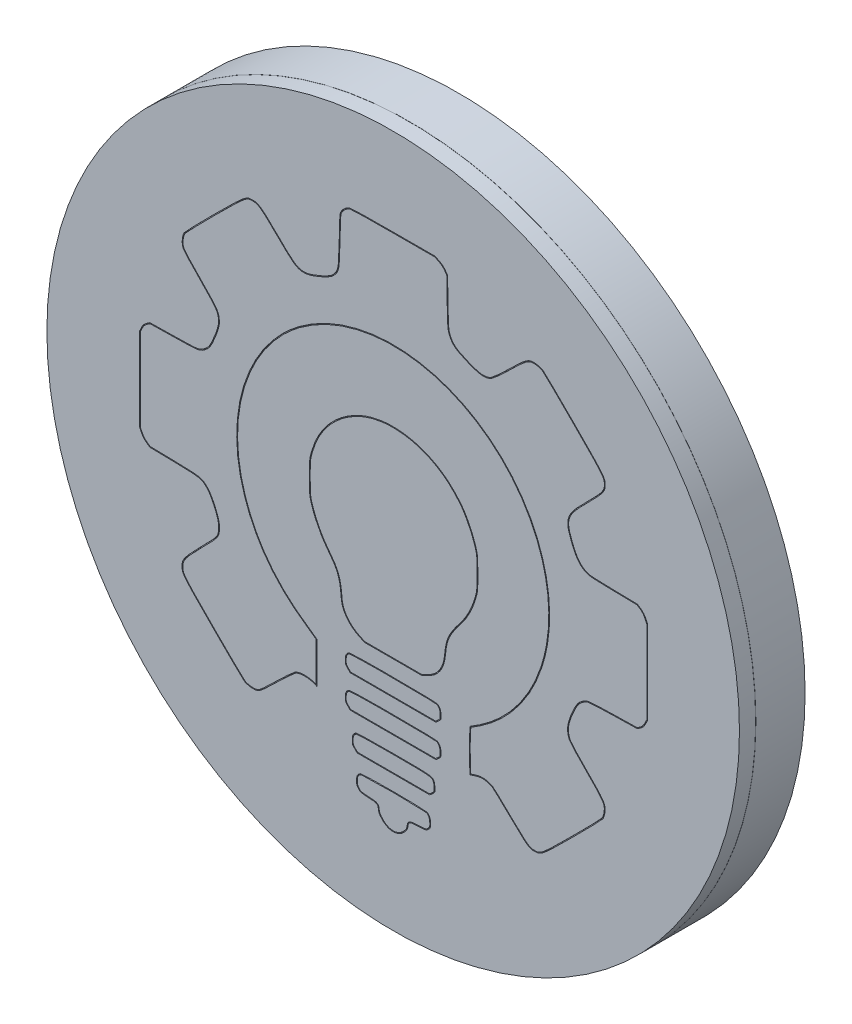
SolidWorks part; units mm, degrees
ref_plane "Front Plane" through (0, 0, 0) normal (0, 0, 1) x (1, 0, 0)
ref_plane "Top Plane" through (0, 0, 0) normal (0, 1, 0) x (1, 0, 0)
ref_plane "Right Plane" through (0, 0, 0) normal (1, 0, 0) x (0, 0, -1)
sketch "Sketch1" plane through (0, 0, 0) normal (0, 0, 1) x (1, 0, 0)
  circle A0 centre (0, 0) radius 20.1
  circle A1 centre (0, 0) radius 21.1
  dimension "D1" = 40.2
  dimension "D2" = 1
extrude "Boss-Extrude1" add sketch "Sketch1" along normal blind 3
sketch "Sketch2" plane through (0, 0, 3) normal (0, 0, 1) x (1, 0, 0)
  circle A0 centre (0, 0) radius 21.1
  circle A1 centre (0, 0) radius 21.1 construction
  point P8 (0, 0)
  circle M3 centre (0, 0) radius 21.1
  circle M4 centre (0, 0) radius 20.1
extrude "Boss-Extrude3" add sketch "Sketch2" along normal blind 1 contours M3 M4 | M4 region at (-20.5032, 0, 3) region at (0, 0, 3)
sketch "Sketch4" plane through (0, 0, 4) normal (0, 0, 1) x (1, 0, 0)
  line L0 (-2.0843, -6.5936) -> (-1.7501, -6.7532)
  line L1 (-1.7501, -6.7532) -> (0, -6.7532)
  line L2 (0, -6.7532) -> (1.7501, -6.7532)
  line L3 (1.7501, -6.7532) -> (2.0845, -6.5935)
  line L4 (-2.3423, -12.6615) -> (-2.1917, -12.8122)
  line L5 (-2.1917, -12.8122) -> (0.0212, -12.8122)
  line L6 (0.0212, -12.8122) -> (2.233, -12.8122)
  line L7 (2.233, -12.8122) -> (2.3945, -12.6731)
  line L8 (-2.7656, -10.613) -> (-2.615, -10.7636)
  line L9 (-2.615, -10.7636) -> (-0.0053, -10.7636)
  line L10 (-0.0053, -10.7636) -> (2.6034, -10.7636)
  line L11 (2.6034, -10.7636) -> (2.7649, -10.6246)
  line L12 (-2.7656, -8.6399) -> (-2.615, -8.7905)
  line L13 (-2.615, -8.7905) -> (-0.0053, -8.7905)
  line L14 (-0.0053, -8.7905) -> (2.6034, -8.7905)
  line L15 (2.6034, -8.7905) -> (2.7649, -8.6515)
  line L16 (-13.3914, 3.6037) -> (-14.8226, 3.5778)
  line L17 (-14.8226, 3.5778) -> (-15.0198, 3.4463)
  line L18 (-15.3402, 3.0628) -> (-15.4575, 2.8086)
  line L19 (-15.4575, 2.8086) -> (-15.4575, 0.2853)
  line L20 (-15.4575, 0.2853) -> (-15.4575, -2.2316)
  line L21 (-15.4575, -2.2316) -> (-15.3359, -2.4797)
  line L22 (-15.0144, -2.86) -> (-14.8211, -2.9967)
  line L23 (-14.8211, -2.9967) -> (-13.3914, -3.0226)
  line L24 (-4.7581, -10.4769) -> (-4.6508, -10.5272)
  line L25 (-4.6508, -10.5272) -> (-4.6508, -9.3615)
  line L26 (13.444, -3.0279) -> (14.8751, -2.9968)
  line L27 (14.8751, -2.9968) -> (15.0633, -2.8697)
  line L28 (15.3835, -2.4903) -> (15.5104, -2.2315)
  line L29 (15.5104, -2.2315) -> (15.5104, 0.2853)
  line L30 (15.5104, 0.2853) -> (15.5104, 2.8086)
  line L31 (15.5104, 2.8086) -> (15.3931, 3.0628)
  line L32 (15.0728, 3.4463) -> (14.8755, 3.5778)
  line L33 (14.8755, 3.5778) -> (13.4442, 3.6037)
  line L34 (3.3396, 13.7349) -> (3.3137, 15.1393)
  line L35 (3.3137, 15.1393) -> (3.1868, 15.3274)
  line L36 (2.8073, 15.6476) -> (2.5486, 15.7745)
  line L37 (2.5486, 15.7745) -> (0.0317, 15.7692)
  line L76 (-13.3905, 3.5537) -> (-14.8071, 3.528)
  line L77 (-14.8071, 3.528) -> (-14.9917, 3.4049)
  line L78 (-15.2949, 3.0417) -> (-15.4075, 2.7976)
  line L79 (-15.4075, 2.7976) -> (-15.4075, 0.2853)
  line L80 (-15.4075, 0.2853) -> (-15.4075, -2.22)
  line L81 (-15.4075, -2.22) -> (-15.2911, -2.4575)
  line L82 (-14.9863, -2.8186) -> (-14.8048, -2.947)
  line L83 (-14.8048, -2.947) -> (-13.3905, -2.9726)
  line L84 (-4.7374, -10.4314) -> (-4.7008, -10.4485)
  line L85 (-4.7008, -10.4485) -> (-4.7008, -9.3615)
  line L86 (13.4429, -2.9779) -> (14.8593, -2.9471)
  line L87 (14.8593, -2.9471) -> (15.0353, -2.8283)
  line L88 (15.3387, -2.4681) -> (15.4604, -2.2199)
  line L89 (15.4604, -2.2199) -> (15.4604, 0.2853)
  line L90 (15.4604, 0.2853) -> (15.4604, 2.7976)
  line L91 (15.4604, 2.7976) -> (15.3478, 3.0417)
  line L92 (15.0447, 3.4049) -> (14.86, 3.528)
  line L93 (14.86, 3.528) -> (13.4433, 3.5537)
  line L94 (3.2896, 13.7339) -> (3.264, 15.1236)
  line L95 (3.264, 15.1236) -> (3.1453, 15.2994)
  line L96 (2.7851, 15.6028) -> (2.5371, 15.7244)
  line L97 (2.5371, 15.7244) -> (0.0318, 15.7192)
  line L98 (-2.0627, -6.5484) -> (-1.7387, -6.7032)
  line L99 (-1.7387, -6.7032) -> (0, -6.7032)
  line L100 (0, -6.7032) -> (1.7387, -6.7032)
  line L101 (1.7387, -6.7032) -> (2.063, -6.5483)
  line L102 (-2.7303, -8.6045) -> (-2.5943, -8.7405)
  line L103 (-2.5943, -8.7405) -> (-0.0053, -8.7405)
  line L104 (-0.0053, -8.7405) -> (2.5849, -8.7405)
  line L105 (2.5849, -8.7405) -> (2.7318, -8.614)
  line L106 (-2.7303, -10.5777) -> (-2.5943, -10.7136)
  line L107 (-2.5943, -10.7136) -> (-0.0053, -10.7136)
  line L108 (-0.0053, -10.7136) -> (2.5849, -10.7136)
  line L109 (2.5849, -10.7136) -> (2.7318, -10.5871)
  line L110 (-2.3069, -12.6262) -> (-2.171, -12.7622)
  line L111 (-2.171, -12.7622) -> (0.0212, -12.7622)
  line L112 (0.0212, -12.7622) -> (2.2144, -12.7622)
  line L113 (2.2144, -12.7622) -> (2.3614, -12.6356)
  spline S0 degree 1 poles (2.0845, -6.5935) (3.1918, -4.9021) knots 0 0 1 1 construction
  spline S1 degree 1 poles (3.1918, -4.9021) (4.1812, -2.7697) knots 0 0 1 1 construction
  spline S2 degree 1 poles (4.1812, -2.7697) (5.0161, -1.1091) knots 0 0 1 1 construction
  spline S3 degree 1 poles (5.0161, -1.1091) (5.1599, 0.317) knots 0 0 1 1 construction
  spline S4 degree 1 poles (5.1599, 0.317) (5.0214, 1.7323) knots 0 0 1 1 construction
  spline S5 degree 1 poles (5.0214, 1.7323) (4.19, 3.4113) knots 0 0 1 1 construction
  spline S6 degree 1 poles (4.19, 3.4113) (-0.7532, 5.4515) knots 0 0 1 1 construction
  spline S7 degree 1 poles (-0.7532, 5.4515) (-4.2876, 3.1932) knots 0 0 1 1 construction
  spline S8 degree 1 poles (-4.2876, 3.1932) (-4.9686, 1.7215) knots 0 0 1 1 construction
  spline S9 degree 1 poles (-4.9686, 1.7215) (-5.107, 0.317) knots 0 0 1 1 construction
  spline S10 degree 1 poles (-5.107, 0.317) (-4.9685, -1.1037) knots 0 0 1 1 construction
  spline S11 degree 1 poles (-4.9685, -1.1037) (-4.0601, -2.8748) knots 0 0 1 1 construction
  spline S12 degree 1 poles (-4.0601, -2.8748) (-3.1864, -4.8979) knots 0 0 1 1 construction
  spline S13 degree 1 poles (-3.1864, -4.8979) (-3.0112, -5.6926) knots 0 0 1 1 construction
  spline S14 degree 1 poles (-3.0112, -5.6926) (-2.0843, -6.5936) knots 0 0 1 1 construction
  spline S15 degree 3 poles (2.0845, -6.5935) (2.2455, -6.5177) (2.5637, -6.3226) (2.8833, -5.9594) (3.0989, -5.509) (3.1741, -5.0978) (3.1918, -4.9021) knots -0.000046 -0.000046 -0.000046 -0.000046 0.249973 0.499993 0.750012 1.000031 1.000031 1.000031 1.000031
  spline S16 degree 3 poles (3.1918, -4.9021) (3.2087, -4.7187) (3.2601, -4.335) (3.415, -3.8828) (3.6533, -3.4762) (3.9187, -3.1067) (4.0962, -2.8773) (4.1812, -2.7697) knots -0.000035 -0.000035 -0.000035 -0.000035 0.249965 0.499966 0.749966 0.874966 0.999966 0.999966 0.999966 0.999966
  spline S17 degree 3 poles (4.1812, -2.7697) (4.2699, -2.6568) (4.4299, -2.4273) (4.6592, -2.0208) (4.8579, -1.5803) (4.9683, -1.2667) (5.0161, -1.1091) knots 0.000077 0.000077 0.000077 0.000077 0.250072 0.500067 0.750063 1.000058 1.000058 1.000058 1.000058
  spline S18 degree 3 poles (5.0161, -1.1091) (5.0446, -1.0158) (5.1045, -0.8128) (5.1411, -0.5964) (5.1559, -0.3187) (5.1596, -0.0073) (5.1599, 0.2144) (5.1599, 0.317) knots -0.00008 -0.00008 -0.00008 -0.00008 0.24994 0.49996 0.74998 0.87499 1 1 1 1
  spline S19 degree 3 poles (5.1599, 0.317) (5.1599, 0.4192) (5.1596, 0.6397) (5.156, 0.9509) (5.1416, 1.2295) (5.1062, 1.446) (5.049, 1.6418) (5.0214, 1.7323) knots 0 0 0 0 0.124986 0.249972 0.499943 0.749915 0.999887 0.999887 0.999887 0.999887
  spline S20 degree 3 poles (5.0214, 1.7323) (4.9758, 1.8802) (4.8726, 2.1623) (4.6647, 2.6258) (4.4258, 3.0651) (4.2762, 3.2955) (4.19, 3.4113) knots 0.000095 0.000095 0.000095 0.000095 0.250106 0.500117 0.750127 1.000138 1.000138 1.000138 1.000138
  spline S21 degree 3 poles (4.19, 3.4113) (3.9138, 3.786) (3.2489, 4.4626) (2.0372, 5.1579) (0.6812, 5.5223) (-0.2849, 5.5178) (-0.7532, 5.4515) knots -0.000037 -0.000037 -0.000037 -0.000037 0.24997 0.499977 0.749983 0.99999 0.99999 0.99999 0.99999
  spline S22 degree 3 poles (-0.7532, 5.4515) (-1.1014, 5.4017) (-1.7815, 5.2206) (-2.7559, 4.7277) (-3.6193, 4.0467) (-4.087, 3.4928) (-4.2876, 3.1932) knots 0.000014 0.000014 0.000014 0.000014 0.24999 0.499967 0.749943 0.99992 0.99992 0.99992 0.99992
  spline S23 degree 3 poles (-4.2876, 3.1932) (-4.3628, 3.0792) (-4.5131, 2.8388) (-4.6803, 2.5149) (-4.8248, 2.1682) (-4.9245, 1.8656) (-4.9686, 1.7215) knots 0.000188 0.000188 0.000188 0.000188 0.250177 0.500166 0.750155 1.000144 1.000144 1.000144 1.000144
  spline S24 degree 3 poles (-4.9686, 1.7215) (-4.9963, 1.6329) (-5.0532, 1.4417) (-5.0887, 1.2265) (-5.1031, 0.9484) (-5.1067, 0.6381) (-5.107, 0.4187) (-5.107, 0.317) knots -0.000217 -0.000217 -0.000217 -0.000217 0.249837 0.499891 0.749946 0.874973 1 1 1 1
  spline S25 degree 3 poles (-5.107, 0.317) (-5.107, 0.2144) (-5.1067, -0.0074) (-5.1031, -0.3195) (-5.0887, -0.5981) (-5.0533, -0.8143) (-4.996, -1.0123) (-4.9685, -1.1037) knots 0 0 0 0 0.124966 0.249933 0.499865 0.749798 0.99973 0.99973 0.99973 0.99973
  spline S26 degree 3 poles (-4.9685, -1.1037) (-4.9194, -1.2623) (-4.8065, -1.5619) (-4.5732, -2.0647) (-4.306, -2.5351) (-4.1524, -2.7604) (-4.0601, -2.8748) knots 0.00022 0.00022 0.00022 0.00022 0.250216 0.500211 0.750207 1.000202 1.000202 1.000202 1.000202
  spline S27 degree 3 poles (-4.0601, -2.8748) (-3.987, -2.9665) (-3.836, -3.1609) (-3.605, -3.4879) (-3.3937, -3.8638) (-3.2741, -4.2505) (-3.2157, -4.5954) (-3.1946, -4.7995) (-3.1864, -4.8979) knots -0.000102 -0.000102 -0.000102 -0.000102 0.124929 0.24996 0.500021 0.750083 0.875114 1.000144 1.000144 1.000144 1.000144
  spline S28 degree 3 poles (-3.1864, -4.8979) (-3.1796, -4.9878) (-3.1613, -5.1842) (-3.1278, -5.376) (-3.0821, -5.536) (-3.0361, -5.6415) (-3.0112, -5.6926) knots -0.000267 -0.000267 -0.000267 -0.000267 0.249732 0.499731 0.74973 0.999729 0.999729 0.999729 0.999729
  spline S29 degree 3 poles (-3.0112, -5.6926) (-2.9634, -5.7894) (-2.8506, -5.9741) (-2.6343, -6.2222) (-2.3782, -6.4334) (-2.1846, -6.5459) (-2.0843, -6.5936) knots 0.000158 0.000158 0.000158 0.000158 0.250127 0.500096 0.750065 1.000034 1.000034 1.000034 1.000034
  spline S30 degree 1 poles (-2.0082, -13.8112) (-2.2337, -14.2488) knots 0 0 1 1 construction
  spline S31 degree 1 poles (-2.2337, -14.2488) (-2.0488, -14.7173) knots 0 0 1 1 construction
  spline S32 degree 1 poles (-2.0488, -14.7173) (-1.5135, -14.8231) knots 0 0 1 1 construction
  spline S33 degree 1 poles (-1.5135, -14.8231) (-0.9171, -15.0403) knots 0 0 1 1 construction
  spline S34 degree 1 poles (-0.9171, -15.0403) (-0.7031, -15.5234) knots 0 0 1 1 construction
  spline S35 degree 1 poles (-0.7031, -15.5234) (0.7031, -15.5234) knots 0 0 1 1 construction
  spline S36 degree 1 poles (0.7031, -15.5234) (0.9171, -15.0403) knots 0 0 1 1 construction
  spline S37 degree 1 poles (0.9171, -15.0403) (1.5395, -14.8232) knots 0 0 1 1 construction
  spline S38 degree 1 poles (1.5395, -14.8232) (2.1478, -14.6711) knots 0 0 1 1 construction
  spline S39 degree 1 poles (2.1478, -14.6711) (2.2813, -14.3356) knots 0 0 1 1 construction
  spline S40 degree 1 poles (2.2813, -14.3356) (2.0685, -13.8174) knots 0 0 1 1 construction
  spline S41 degree 1 poles (2.0685, -13.8174) (-2.0082, -13.8112) knots 0 0 1 1 construction
  spline S42 degree 3 poles (-2.0082, -13.8112) (-2.043, -13.8322) (-2.1113, -13.8822) (-2.1776, -13.9737) (-2.2208, -14.0865) (-2.2326, -14.1974) (-2.2337, -14.2488) knots 0.006401 0.006401 0.006401 0.006401 0.255102 0.503803 0.752504 1.001206 1.001206 1.001206 1.001206
  spline S43 degree 3 poles (-2.2337, -14.2488) (-2.2358, -14.3001) (-2.2338, -14.4135) (-2.2054, -14.5191) (-2.1551, -14.6112) (-2.0836, -14.6856) (-2.0488, -14.7173) knots -0.001199 -0.001199 -0.001199 -0.001199 0.249371 0.499941 0.750511 1.001081 1.001081 1.001081 1.001081
  spline S44 degree 3 poles (-2.0488, -14.7173) (-2.0331, -14.732) (-2.0026, -14.7547) (-1.9152, -14.7841) (-1.7714, -14.8064) (-1.5926, -14.8187) (-1.5135, -14.8231) knots -0.001587 -0.001587 -0.001587 -0.001587 0.248739 0.499065 0.749392 0.999718 0.999718 0.999718 0.999718
  spline S45 degree 3 poles (-1.5135, -14.8231) (-1.4252, -14.8274) (-1.2207, -14.8401) (-1.0826, -14.8571) (-0.9499, -14.9221) (-0.9237, -15.001) (-0.9171, -15.0403) knots 0.000245 0.000245 0.000245 0.000245 0.251684 0.503123 0.754563 1.006002 1.006002 1.006002 1.006002
  spline S46 degree 3 poles (-0.9171, -15.0403) (-0.9096, -15.0952) (-0.8897, -15.2185) (-0.8555, -15.3178) (-0.8074, -15.4038) (-0.7362, -15.487) (-0.7031, -15.5234) knots -0.001538 -0.001538 -0.001538 -0.001538 0.249242 0.500023 0.750803 1.001583 1.001583 1.001583 1.001583
  spline S47 degree 3 poles (-0.7031, -15.5234) (-0.6105, -15.6303) (-0.3707, -15.8193) (0, -15.8965) (0.3707, -15.8193) (0.6105, -15.6303) (0.7031, -15.5234) knots -0.000592 -0.000592 -0.000592 -0.000592 0.249704 0.5 0.750296 1.000592 1.000592 1.000592 1.000592
  spline S48 degree 3 poles (0.7031, -15.5234) (0.7362, -15.487) (0.8074, -15.4038) (0.8555, -15.3178) (0.8897, -15.2185) (0.9096, -15.0952) (0.9171, -15.0403) knots -0.001583 -0.001583 -0.001583 -0.001583 0.249198 0.499979 0.75076 1.001541 1.001541 1.001541 1.001541
  spline S49 degree 3 poles (0.9171, -15.0403) (0.9238, -15.0002) (0.9539, -14.919) (1.0836, -14.8597) (1.2159, -14.8451) (1.3755, -14.8328) (1.4875, -14.8262) (1.5395, -14.8232) knots -0.006038 -0.006038 -0.006038 -0.006038 0.245488 0.497014 0.748539 0.874302 1.000065 1.000065 1.000065 1.000065
  spline S50 degree 3 poles (1.5395, -14.8232) (1.5924, -14.8202) (1.7068, -14.8136) (1.8658, -14.8016) (1.9903, -14.7813) (2.0598, -14.7518) (2.1213, -14.6967) (2.1478, -14.6711) knots -0.000062 -0.000062 -0.000062 -0.000062 0.124957 0.249976 0.500015 0.750053 1.000092 1.000092 1.000092 1.000092
  spline S51 degree 3 poles (2.1478, -14.6711) (2.1738, -14.6461) (2.2312, -14.5863) (2.26, -14.5329) (2.2779, -14.4704) (2.2813, -14.3762) (2.2813, -14.3356) knots -0.000104 -0.000104 -0.000104 -0.000104 0.249922 0.499948 0.749974 1 1 1 1
  spline S52 degree 3 poles (2.2813, -14.3356) (2.2813, -14.2693) (2.2713, -14.1248) (2.2282, -13.9824) (2.1634, -13.8803) (2.1016, -13.8356) (2.0685, -13.8174) knots 0 0 0 0 0.249288 0.498577 0.747865 0.997153 0.997153 0.997153 0.997153
  spline S53 degree 3 poles (2.0685, -13.8174) (2.04, -13.8107) (1.9998, -13.8046) (1.7761, -13.7842) (1.377, -13.767) (0.7442, -13.753) (0.0407, -13.7477) (-0.6646, -13.7507) (-1.2989, -13.7624) (-1.7075, -13.7791) (-1.9282, -13.7973) (-1.9768, -13.8043) (-2.0082, -13.8112) knots 0.023161 0.023161 0.023161 0.023161 0.0824 0.14164 0.260119 0.378598 0.497077 0.615557 0.734036 0.852515 0.911754 0.970994 0.970994 0.970994 0.970994
  spline S54 degree 1 poles (2.3945, -12.6731) (2.5458, -12.3248) knots 0 0 1 1 construction
  spline S55 degree 1 poles (2.5458, -12.3248) (2.4922, -11.9766) knots 0 0 1 1 construction
  spline S56 degree 1 poles (2.4922, -11.9766) (0.0161, -11.7422) knots 0 0 1 1 construction
  spline S57 degree 1 poles (0.0161, -11.7422) (-2.2574, -11.7952) knots 0 0 1 1 construction
  spline S58 degree 1 poles (-2.2574, -11.7952) (-2.4929, -12.2666) knots 0 0 1 1 construction
  spline S59 degree 1 poles (-2.4929, -12.2666) (-2.3423, -12.6615) knots 0 0 1 1 construction
  spline S60 degree 3 poles (2.3945, -12.6731) (2.4251, -12.6454) (2.4956, -12.5779) (2.5253, -12.5268) (2.543, -12.4695) (2.5458, -12.3678) (2.5458, -12.3248) knots 0.001503 0.001503 0.001503 0.001503 0.251127 0.500751 0.750376 1 1 1 1
  spline S61 degree 3 poles (2.5458, -12.3248) (2.5458, -12.291) (2.5427, -12.225) (2.5304, -12.1172) (2.5098, -12.0225) (2.5008, -11.9938) (2.4922, -11.9766) knots 0 0 0 0 0.2514 0.5028 0.7542 1.0056 1.0056 1.0056 1.0056
  spline S62 degree 3 poles (2.4922, -11.9766) (2.4796, -11.9494) (2.4501, -11.888) (2.4104, -11.8481) (2.3354, -11.8117) (2.1571, -11.7778) (1.8666, -11.7573) (1.438, -11.7463) (0.9389, -11.743) (0.4516, -11.7422) (0.157, -11.7422) (0.0161, -11.7422) knots -0.00138 -0.00138 -0.00138 -0.00138 0.123789 0.248959 0.374128 0.499298 0.624468 0.749637 0.874807 0.937392 0.999976 0.999976 0.999976 0.999976
  spline S63 degree 3 poles (0.0161, -11.7422) (-0.1488, -11.7427) (-0.4935, -11.7443) (-1.0624, -11.7487) (-1.6356, -11.757) (-2.0078, -11.7701) (-2.1922, -11.7842) (-2.2315, -11.7899) (-2.2574, -11.7952) knots 0.000038 0.000038 0.000038 0.000038 0.11625 0.232461 0.464885 0.697309 0.813521 0.929733 0.929733 0.929733 0.929733
  spline S64 degree 3 poles (-2.2574, -11.7952) (-2.2959, -11.8167) (-2.3737, -11.8696) (-2.4406, -11.9613) (-2.483, -12.0786) (-2.4929, -12.208) (-2.4929, -12.2666) knots 0.001931 0.001931 0.001931 0.001931 0.251448 0.500965 0.750483 1 1 1 1
  spline S65 degree 3 poles (-2.4929, -12.2666) (-2.4929, -12.3156) (-2.4901, -12.4305) (-2.4714, -12.5005) (-2.4405, -12.5592) (-2.3724, -12.6315) (-2.3423, -12.6615) knots 0 0 0 0 0.25 0.5 0.75 1 1 1 1
  spline S66 degree 1 poles (2.7649, -10.6246) (2.9163, -10.271) knots 0 0 1 1 construction
  spline S67 degree 1 poles (2.9163, -10.271) (2.6781, -9.745) knots 0 0 1 1 construction
  spline S68 degree 1 poles (2.6781, -9.745) (-2.6842, -9.7486) knots 0 0 1 1 construction
  spline S69 degree 1 poles (-2.6842, -9.7486) (-2.9163, -10.2181) knots 0 0 1 1 construction
  spline S70 degree 1 poles (-2.9163, -10.2181) (-2.7656, -10.613) knots 0 0 1 1 construction
  spline S71 degree 3 poles (2.7649, -10.6246) (2.7956, -10.5969) (2.8667, -10.5294) (2.8956, -10.4798) (2.9134, -10.4225) (2.9163, -10.3158) (2.9163, -10.271) knots 0.001495 0.001495 0.001495 0.001495 0.251121 0.500747 0.750374 1 1 1 1
  spline S72 degree 3 poles (2.9163, -10.271) (2.9163, -10.2075) (2.9033, -10.0735) (2.8503, -9.92) (2.7731, -9.8062) (2.7124, -9.7627) (2.6781, -9.745) knots 0 0 0 0 0.247513 0.495027 0.74254 0.990053 0.990053 0.990053 0.990053
  spline S73 degree 3 poles (2.6781, -9.745) (2.6412, -9.7391) (2.5896, -9.7343) (2.3016, -9.7182) (1.7773, -9.7051) (0.9398, -9.6949) (0.0052, -9.6919) (-0.9305, -9.6955) (-1.7709, -9.7065) (-2.2994, -9.7203) (-2.5914, -9.7372) (-2.646, -9.7425) (-2.6842, -9.7486) knots 0.023969 0.023969 0.023969 0.023969 0.083123 0.142277 0.260585 0.378892 0.4972 0.615508 0.733816 0.852123 0.911277 0.970431 0.970431 0.970431 0.970431
  spline S74 degree 3 poles (-2.6842, -9.7486) (-2.722, -9.7701) (-2.7982, -9.8224) (-2.8646, -9.9142) (-2.9065, -10.031) (-2.9163, -10.1598) (-2.9163, -10.2181) knots 0.007864 0.007864 0.007864 0.007864 0.255898 0.503932 0.751966 1 1 1 1
  spline S75 degree 3 poles (-2.9163, -10.2181) (-2.9163, -10.267) (-2.9135, -10.3819) (-2.8948, -10.452) (-2.8638, -10.5107) (-2.7957, -10.5829) (-2.7656, -10.613) knots 0 0 0 0 0.25 0.5 0.75 1 1 1 1
  spline S76 degree 1 poles (2.7649, -8.6515) (2.9163, -8.2978) knots 0 0 1 1 construction
  spline S77 degree 1 poles (2.9163, -8.2978) (2.6879, -7.7768) knots 0 0 1 1 construction
  spline S78 degree 1 poles (2.6879, -7.7768) (-2.6833, -7.775) knots 0 0 1 1 construction
  spline S79 degree 1 poles (-2.6833, -7.775) (-2.9163, -8.2449) knots 0 0 1 1 construction
  spline S80 degree 1 poles (-2.9163, -8.2449) (-2.7656, -8.6399) knots 0 0 1 1 construction
  spline S81 degree 3 poles (2.7649, -8.6515) (2.7956, -8.6237) (2.8667, -8.5562) (2.8956, -8.5066) (2.9134, -8.4494) (2.9163, -8.3427) (2.9163, -8.2978) knots 0.001495 0.001495 0.001495 0.001495 0.251121 0.500747 0.750374 1 1 1 1
  spline S82 degree 3 poles (2.9163, -8.2978) (2.9163, -8.2322) (2.9047, -8.0912) (2.8561, -7.9423) (2.7842, -7.8355) (2.7221, -7.7934) (2.6879, -7.7768) knots 0 0 0 0 0.248876 0.497751 0.746627 0.995502 0.995502 0.995502 0.995502
  spline S83 degree 3 poles (2.6879, -7.7768) (2.6517, -7.7704) (2.6017, -7.7655) (2.3139, -7.7479) (1.7893, -7.7334) (0.95, -7.7216) (0.0131, -7.7173) (-0.9252, -7.7202) (-1.7682, -7.7311) (-2.2982, -7.7453) (-2.5911, -7.763) (-2.6452, -7.7685) (-2.6833, -7.775) knots 0.022815 0.022815 0.022815 0.022815 0.082071 0.141327 0.25984 0.378353 0.496866 0.615379 0.733891 0.852404 0.911661 0.970917 0.970917 0.970917 0.970917
  spline S84 degree 3 poles (-2.6833, -7.775) (-2.7213, -7.7965) (-2.7979, -7.8489) (-2.8644, -7.9407) (-2.9064, -8.0576) (-2.9163, -8.1865) (-2.9163, -8.2449) knots 0.006322 0.006322 0.006322 0.006322 0.254742 0.503161 0.751581 1 1 1 1
  spline S85 degree 3 poles (-2.9163, -8.2449) (-2.9163, -8.2939) (-2.9135, -8.4088) (-2.8948, -8.4789) (-2.8638, -8.5376) (-2.7957, -8.6098) (-2.7656, -8.6399) knots 0 0 0 0 0.25 0.5 0.75 1 1 1 1
  spline S86 degree 1 poles (-15.0198, 3.4463) (-15.3402, 3.0628) knots 0 0 1 1 construction
  spline S87 degree 1 poles (-15.3359, -2.4797) (-15.0144, -2.86) knots 0 0 1 1 construction
  spline S88 degree 1 poles (-13.3914, -3.0226) (-11.28, -3.4861) knots 0 0 1 1 construction
  spline S89 degree 1 poles (-11.28, -3.4861) (-10.6491, -4.8873) knots 0 0 1 1 construction
  spline S90 degree 1 poles (-10.6491, -4.8873) (-10.6547, -5.4075) knots 0 0 1 1 construction
  spline S91 degree 1 poles (-10.6547, -5.4075) (-11.7083, -6.6855) knots 0 0 1 1 construction
  spline S92 degree 1 poles (-11.7083, -6.6855) (-12.8646, -8.2509) knots 0 0 1 1 construction
  spline S93 degree 1 poles (-12.8646, -8.2509) (-10.9939, -10.5822) knots 0 0 1 1 construction
  spline S94 degree 1 poles (-10.9939, -10.5822) (-9.0654, -12.4617) knots 0 0 1 1 construction
  spline S95 degree 1 poles (-9.0654, -12.4617) (-8.2536, -12.5523) knots 0 0 1 1 construction
  spline S96 degree 1 poles (-8.2536, -12.5523) (-7.108, -11.5444) knots 0 0 1 1 construction
  spline S97 degree 1 poles (-7.108, -11.5444) (-5.9205, -10.4637) knots 0 0 1 1 construction
  spline S98 degree 1 poles (-5.9205, -10.4637) (-4.7581, -10.4769) knots 0 0 1 1 construction
  spline S99 degree 1 poles (-4.6508, -9.3615) (-4.6424, -8.0386) knots 0 0 1 1 construction
  spline S100 degree 1 poles (-4.6424, -8.0386) (-5.2045, -7.6348) knots 0 0 1 1 construction
  spline S101 degree 1 poles (-5.2045, -7.6348) (-9.0061, -2.6725) knots 0 0 1 1 construction
  spline S102 degree 1 poles (-9.0061, -2.6725) (-5.7169, 7.8688) knots 0 0 1 1 construction
  spline S103 degree 1 poles (-5.7169, 7.8688) (5.0536, 8.3235) knots 0 0 1 1 construction
  spline S104 degree 1 poles (5.0536, 8.3235) (9.0115, -2.6511) knots 0 0 1 1 construction
  spline S105 degree 1 poles (9.0115, -2.6511) (5.2624, -7.5979) knots 0 0 1 1 construction
  spline S106 degree 1 poles (5.2624, -7.5979) (4.6862, -7.9646) knots 0 0 1 1 construction
  spline S107 degree 1 poles (4.6862, -7.9646) (4.6816, -10.5305) knots 0 0 1 1 construction
  spline S108 degree 1 poles (4.6816, -10.5305) (4.9675, -10.4365) knots 0 0 1 1 construction
  spline S109 degree 1 poles (4.9675, -10.4365) (6, -10.4796) knots 0 0 1 1 construction
  spline S110 degree 1 poles (6, -10.4796) (7.1347, -11.5235) knots 0 0 1 1 construction
  spline S111 degree 1 poles (7.1347, -11.5235) (8.5778, -12.6005) knots 0 0 1 1 construction
  spline S112 degree 1 poles (8.5778, -12.6005) (10.8991, -10.7299) knots 0 0 1 1 construction
  spline S113 degree 1 poles (10.8991, -10.7299) (12.7783, -8.8019) knots 0 0 1 1 construction
  spline S114 degree 1 poles (12.7783, -8.8019) (12.9025, -8.4066) knots 0 0 1 1 construction
  spline S115 degree 1 poles (12.9025, -8.4066) (11.8196, -6.7704) knots 0 0 1 1 construction
  spline S116 degree 1 poles (11.8196, -6.7704) (10.7668, -5.6019) knots 0 0 1 1 construction
  spline S117 degree 1 poles (10.7668, -5.6019) (10.8875, -4.3023) knots 0 0 1 1 construction
  spline S118 degree 1 poles (10.8875, -4.3023) (11.8122, -3.1267) knots 0 0 1 1 construction
  spline S119 degree 1 poles (11.8122, -3.1267) (13.444, -3.0279) knots 0 0 1 1 construction
  spline S120 degree 1 poles (15.0633, -2.8697) (15.3835, -2.4903) knots 0 0 1 1 construction
  spline S121 degree 1 poles (15.3931, 3.0628) (15.0728, 3.4463) knots 0 0 1 1 construction
  spline S122 degree 1 poles (13.4442, 3.6037) (11.7175, 3.7577) knots 0 0 1 1 construction
  spline S123 degree 1 poles (11.7175, 3.7577) (10.9191, 4.8572) knots 0 0 1 1 construction
  spline S124 degree 1 poles (10.9191, 4.8572) (11.8624, 7.4261) knots 0 0 1 1 construction
  spline S125 degree 1 poles (11.8624, 7.4261) (12.9175, 8.8321) knots 0 0 1 1 construction
  spline S126 degree 1 poles (12.9175, 8.8321) (11.0468, 11.1633) knots 0 0 1 1 construction
  spline S127 degree 1 poles (11.0468, 11.1633) (9.1189, 13.0424) knots 0 0 1 1 construction
  spline S128 degree 1 poles (9.1189, 13.0424) (8.7236, 13.1666) knots 0 0 1 1 construction
  spline S129 degree 1 poles (8.7236, 13.1666) (7.0817, 12.0938) knots 0 0 1 1 construction
  spline S130 degree 1 poles (7.0817, 12.0938) (5.8968, 11.0463) knots 0 0 1 1 construction
  spline S131 degree 1 poles (5.8968, 11.0463) (4.5974, 11.2048) knots 0 0 1 1 construction
  spline S132 degree 1 poles (4.5974, 11.2048) (3.5032, 12.0048) knots 0 0 1 1 construction
  spline S133 degree 1 poles (3.5032, 12.0048) (3.3396, 13.7349) knots 0 0 1 1 construction
  spline S134 degree 1 poles (3.1868, 15.3274) (2.8073, 15.6476) knots 0 0 1 1 construction
  spline S135 degree 1 poles (0.0317, 15.7692) (-2.6383, 15.717) knots 0 0 1 1 construction
  spline S136 degree 1 poles (-2.6383, 15.717) (-3.1536, 15.3031) knots 0 0 1 1 construction
  spline S137 degree 1 poles (-3.1536, 15.3031) (-3.2867, 13.7294) knots 0 0 1 1 construction
  spline S138 degree 1 poles (-3.2867, 13.7294) (-3.6966, 11.6714) knots 0 0 1 1 construction
  spline S139 degree 1 poles (-3.6966, 11.6714) (-5.2969, 10.9703) knots 0 0 1 1 construction
  spline S140 degree 1 poles (-5.2969, 10.9703) (-7.0344, 12.0836) knots 0 0 1 1 construction
  spline S141 degree 1 poles (-7.0344, 12.0836) (-8.5203, 13.1816) knots 0 0 1 1 construction
  spline S142 degree 1 poles (-8.5203, 13.1816) (-10.8461, 11.3164) knots 0 0 1 1 construction
  spline S143 degree 1 poles (-10.8461, 11.3164) (-12.7258, 9.3824) knots 0 0 1 1 construction
  spline S144 degree 1 poles (-12.7258, 9.3824) (-12.8169, 8.5721) knots 0 0 1 1 construction
  spline S145 degree 1 poles (-12.8169, 8.5721) (-11.7768, 7.3934) knots 0 0 1 1 construction
  spline S146 degree 1 poles (-11.7768, 7.3934) (-10.6421, 5.6775) knots 0 0 1 1 construction
  spline S147 degree 1 poles (-10.6421, 5.6775) (-11.2583, 4.0889) knots 0 0 1 1 construction
  spline S148 degree 1 poles (-11.2583, 4.0889) (-11.6642, 3.7579) knots 0 0 1 1 construction
  spline S149 degree 1 poles (-11.6642, 3.7579) (-13.3914, 3.6037) knots 0 0 1 1 construction
  spline S150 degree 3 poles (-15.0198, 3.4463) (-15.0538, 3.4228) (-15.1202, 3.3713) (-15.2026, 3.2865) (-15.2751, 3.1882) (-15.3206, 3.1043) (-15.3402, 3.0628) knots 0.001432 0.001432 0.001432 0.001432 0.251178 0.500925 0.750671 1.000417 1.000417 1.000417 1.000417
  spline S151 degree 3 poles (-15.3359, -2.4797) (-15.3162, -2.5191) (-15.2721, -2.5951) (-15.1924, -2.702) (-15.1035, -2.7942) (-15.0461, -2.8392) (-15.0144, -2.86) knots -0.000393 -0.000393 -0.000393 -0.000393 0.25058 0.501554 0.752527 1.0035 1.0035 1.0035 1.0035
  spline S152 degree 3 poles (-13.3914, -3.0226) (-13.2942, -3.0245) (-13.0914, -3.0284) (-12.7535, -3.0361) (-12.4027, -3.0475) (-12.0879, -3.0687) (-11.772, -3.114) (-11.511, -3.2219) (-11.3548, -3.3995) (-11.28, -3.4861) knots -0.000028 -0.000028 -0.000028 -0.000028 0.062487 0.125003 0.250033 0.375063 0.500093 0.750154 1.000215 1.000215 1.000215 1.000215
  spline S153 degree 3 poles (-11.28, -3.4861) (-11.2079, -3.5708) (-11.1011, -3.7414) (-10.9017, -4.1299) (-10.7365, -4.5471) (-10.6708, -4.7665) (-10.6491, -4.8873) knots -0.000387 -0.000387 -0.000387 -0.000387 0.249492 0.499372 0.749252 0.999131 0.999131 0.999131 0.999131
  spline S154 degree 3 poles (-10.6491, -4.8873) (-10.6411, -4.928) (-10.6316, -5.008) (-10.6284, -5.1442) (-10.6362, -5.2824) (-10.6472, -5.3653) (-10.6547, -5.4075) knots 0.002368 0.002368 0.002368 0.002368 0.253295 0.504222 0.755148 1.006075 1.006075 1.006075 1.006075
  spline S155 degree 3 poles (-10.6547, -5.4075) (-10.6695, -5.4712) (-10.705, -5.5876) (-10.8464, -5.7919) (-11.0917, -6.0585) (-11.3915, -6.3663) (-11.608, -6.5847) (-11.7083, -6.6855) knots -0.003933 -0.003933 -0.003933 -0.003933 0.247043 0.498019 0.748995 0.874483 0.99997 0.99997 0.99997 0.99997
  spline S156 degree 3 poles (-11.7083, -6.6855) (-11.8211, -6.7996) (-12.062, -7.0453) (-12.4076, -7.4112) (-12.6973, -7.7554) (-12.8427, -8.0212) (-12.8634, -8.1709) (-12.8646, -8.2509) knots 0.000026 0.000026 0.000026 0.000026 0.124943 0.249859 0.499692 0.749525 0.999358 0.999358 0.999358 0.999358
  spline S157 degree 3 poles (-12.8646, -8.2509) (-12.8646, -8.3025) (-12.8635, -8.4144) (-12.836, -8.5681) (-12.7297, -8.762) (-12.4354, -9.1044) (-12.1045, -9.4558) (-11.7154, -9.8534) (-11.3347, -10.2385) (-11.1042, -10.471) (-10.9939, -10.5822) knots 0.000455 0.000455 0.000455 0.000455 0.125397 0.250339 0.500223 0.625165 0.750107 0.875049 0.93752 0.999991 0.999991 0.999991 0.999991
  spline S158 degree 3 poles (-10.9939, -10.5822) (-10.7646, -10.8127) (-10.283, -11.2939) (-9.6849, -11.8821) (-9.3179, -12.2362) (-9.119, -12.4176) (-9.0906, -12.4434) (-9.0654, -12.4617) knots 0.000018 0.000018 0.000018 0.000018 0.245051 0.490084 0.735118 0.857634 0.980151 0.980151 0.980151 0.980151
  spline S159 degree 3 poles (-9.0654, -12.4617) (-9.0115, -12.4949) (-8.9016, -12.5405) (-8.6742, -12.5886) (-8.4393, -12.593) (-8.3161, -12.5727) (-8.2536, -12.5523) knots -0.000665 -0.000665 -0.000665 -0.000665 0.249725 0.500115 0.750505 1.000894 1.000894 1.000894 1.000894
  spline S160 degree 3 poles (-8.2536, -12.5523) (-8.2101, -12.5387) (-8.1599, -12.5081) (-7.9298, -12.33) (-7.6554, -12.0759) (-7.3714, -11.8029) (-7.1925, -11.6276) (-7.108, -11.5444) knots -0.00133 -0.00133 -0.00133 -0.00133 0.249012 0.499355 0.749698 0.874869 1.000041 1.000041 1.000041 1.000041
  spline S161 degree 3 poles (-7.108, -11.5444) (-6.9768, -11.4158) (-6.7025, -11.1507) (-6.3454, -10.8173) (-6.1152, -10.6117) (-5.985, -10.506) (-5.9458, -10.477) (-5.9205, -10.4637) knots -0.000057 -0.000057 -0.000057 -0.000057 0.249885 0.499826 0.749767 0.874738 0.999708 0.999708 0.999708 0.999708
  spline S162 degree 3 poles (-5.9205, -10.4637) (-5.8397, -10.4208) (-5.6684, -10.3691) (-5.3596, -10.3452) (-5.0414, -10.3795) (-4.8501, -10.4363) (-4.7581, -10.4769) knots 0.000147 0.000147 0.000147 0.000147 0.250375 0.500603 0.750831 1.001059 1.001059 1.001059 1.001059
  spline S163 degree 3 poles (-4.6508, -9.3615) (-4.6508, -9.2129) (-4.6503, -8.9018) (-4.6485, -8.519) (-4.6456, -8.2024) (-4.6439, -8.1025) (-4.6424, -8.0386) knots 0 0 0 0 0.214168 0.428337 0.642505 0.856674 0.856674 0.856674 0.856674
  spline S164 degree 3 poles (-4.6424, -8.0386) (-4.6727, -8.014) (-4.7263, -7.9713) (-4.8558, -7.8762) (-5.0159, -7.7629) (-5.143, -7.6761) (-5.2045, -7.6348) knots 0.237673 0.237673 0.237673 0.237673 0.428232 0.618791 0.80935 0.999909 0.999909 0.999909 0.999909
  spline S165 degree 3 poles (-5.2045, -7.6348) (-5.6556, -7.3332) (-6.5262, -6.6511) (-7.5795, -5.4925) (-8.4195, -4.1795) (-8.8389, -3.1794) (-9.0061, -2.6725) knots 0.000017 0.000017 0.000017 0.000017 0.250009 0.500001 0.749994 0.999986 0.999986 0.999986 0.999986
  spline S166 degree 3 poles (-9.0061, -2.6725) (-9.1634, -2.1987) (-9.4028, -1.2178) (-9.5597, 0.743) (-9.1894, 3.1698) (-8.1134, 5.3759) (-6.8696, 6.8987) (-6.1154, 7.5687) (-5.7169, 7.8688) knots 0.000008 0.000008 0.000008 0.000008 0.125007 0.250007 0.500007 0.750006 0.875006 1.000005 1.000005 1.000005 1.000005
  spline S167 degree 3 poles (-5.7169, 7.8688) (-5.3277, 8.161) (-4.497, 8.6905) (-2.7477, 9.4608) (-0.4142, 9.9108) (1.9513, 9.6598) (3.7637, 9.0399) (4.6394, 8.582) (5.0536, 8.3235) knots -0.000006 -0.000006 -0.000006 -0.000006 0.124995 0.249995 0.499996 0.749997 0.874997 0.999997 0.999997 0.999997 0.999997
  spline S168 degree 3 poles (5.0536, 8.3235) (5.5054, 8.0418) (6.3676, 7.3936) (7.8024, 5.868) (9.0736, 3.5816) (9.5564, 1.0072) (9.4279, -1.0891) (9.1789, -2.1434) (9.0115, -2.6511) knots 0.000002 0.000002 0.000002 0.000002 0.125001 0.249999 0.499997 0.749994 0.874992 0.999991 0.999991 0.999991 0.999991
  spline S169 degree 3 poles (9.0115, -2.6511) (8.8466, -3.155) (8.4312, -4.1439) (7.5905, -5.4675) (6.543, -6.6346) (5.7029, -7.3025) (5.2624, -7.5979) knots 0.000018 0.000018 0.000018 0.000018 0.250027 0.500036 0.750045 1.000054 1.000054 1.000054 1.000054
  spline S170 degree 3 poles (5.2624, -7.5979) (5.202, -7.6378) (5.0767, -7.7201) (4.9138, -7.8254) (4.779, -7.9105) (4.72, -7.9452) (4.6862, -7.9646) knots -0.000318 -0.000318 -0.000318 -0.000318 0.209989 0.420296 0.630603 0.84091 0.84091 0.84091 0.84091
  spline S171 degree 3 poles (-14.9917, 3.4049) (-15.024, 3.3827) (-15.0872, 3.3335) (-15.1644, 3.2539) (-15.2325, 3.1618) (-15.2762, 3.0813) (-15.2949, 3.0417) knots 0.002323 0.002323 0.002323 0.002323 0.251742 0.501161 0.750581 1 1 1 1
  spline S172 degree 3 poles (-15.2911, -2.4575) (-15.2723, -2.4951) (-15.23, -2.5678) (-15.1537, -2.6701) (-15.0688, -2.758) (-15.0158, -2.7993) (-14.9863, -2.8186) knots 0 0 0 0 0.25139 0.502779 0.754169 1.005559 1.005559 1.005559 1.005559
  spline S173 degree 3 poles (-13.3905, -2.9726) (-13.2933, -2.9745) (-13.0904, -2.9784) (-12.7522, -2.9861) (-12.4005, -2.9975) (-12.0832, -3.0189) (-11.7607, -3.0646) (-11.478, -3.1822) (-11.3194, -3.364) (-11.242, -3.4536) knots -0.000034 -0.000034 -0.000034 -0.000034 0.062489 0.125013 0.250059 0.375105 0.500152 0.750245 1.000338 1.000338 1.000338 1.000338
  spline S174 degree 3 poles (-11.242, -3.4536) (-11.2077, -3.494) (-11.1489, -3.5749) (-11.0186, -3.7884) (-10.858, -4.1073) (-10.6893, -4.5294) (-10.6221, -4.7545) (-10.6, -4.878) knots -0.000527 -0.000527 -0.000527 -0.000527 0.124393 0.249313 0.499154 0.748994 0.998835 0.998835 0.998835 0.998835
  spline S175 degree 3 poles (-10.6, -4.878) (-10.5915, -4.9209) (-10.5816, -5.0059) (-10.5784, -5.146) (-10.5864, -5.288) (-10.5979, -5.374) (-10.6057, -5.4176) knots 0.003226 0.003226 0.003226 0.003226 0.25457 0.505915 0.757259 1.008604 1.008604 1.008604 1.008604
  spline S176 degree 3 poles (-10.6057, -5.4176) (-10.6214, -5.4854) (-10.6592, -5.6094) (-10.7844, -5.7899) (-10.9544, -5.9831) (-11.1288, -6.1683) (-11.3231, -6.3675) (-11.509, -6.5558) (-11.6196, -6.6672) (-11.6728, -6.7207) knots -0.005543 -0.005543 -0.005543 -0.005543 0.245831 0.497206 0.622893 0.74858 0.874267 0.937111 0.999954 0.999954 0.999954 0.999954
  spline S177 degree 3 poles (-11.6728, -6.7207) (-11.732, -6.7806) (-11.8545, -6.9049) (-12.0639, -7.1204) (-12.2855, -7.3549) (-12.4864, -7.5819) (-12.6796, -7.8278) (-12.7949, -8.0386) (-12.8135, -8.1768) (-12.8146, -8.2513) knots 0.000041 0.000041 0.000041 0.000041 0.062471 0.124902 0.249763 0.374624 0.499485 0.749207 0.998929 0.998929 0.998929 0.998929
  spline S178 degree 3 poles (-12.8146, -8.2513) (-12.8146, -8.3016) (-12.8133, -8.4132) (-12.7944, -8.5141) (-12.7409, -8.638) (-12.6167, -8.8166) (-12.3984, -9.0708) (-12.0683, -9.4213) (-11.6796, -9.8185) (-11.2991, -10.2034) (-11.0687, -10.4358) (-10.9585, -10.5469) knots 0.000773 0.000773 0.000773 0.000773 0.125675 0.250576 0.375478 0.50038 0.625281 0.750183 0.875084 0.937535 0.999986 0.999986 0.999986 0.999986
  spline S179 degree 3 poles (-10.9585, -10.5469) (-10.73, -10.7766) (-10.25, -11.2561) (-9.7549, -11.7433) (-9.4319, -12.0563) (-9.2362, -12.2427) (-9.1205, -12.3497) (-9.0555, -12.4061) (-9.0458, -12.4142) (-9.0376, -12.4201) knots 0.000027 0.000027 0.000027 0.000027 0.244111 0.488195 0.610236 0.732278 0.85432 0.915341 0.976362 0.976362 0.976362 0.976362
  spline S180 degree 3 poles (-9.0376, -12.4201) (-8.9875, -12.4509) (-8.887, -12.4921) (-8.667, -12.539) (-8.4406, -12.5425) (-8.3271, -12.5237) (-8.2688, -12.5047) knots 0.002003 0.002003 0.002003 0.002003 0.251839 0.501675 0.751511 1.001347 1.001347 1.001347 1.001347
  spline S181 degree 3 poles (-8.2688, -12.5047) (-8.2554, -12.5005) (-8.2381, -12.493) (-8.143, -12.4355) (-7.9669, -12.2944) (-7.6897, -12.0397) (-7.4065, -11.7674) (-7.2275, -11.5919) (-7.1431, -11.5087) knots -0.002287 -0.002287 -0.002287 -0.002287 0.123007 0.248301 0.498888 0.749476 0.87477 1.000063 1.000063 1.000063 1.000063
  spline S182 degree 3 poles (-7.1431, -11.5087) (-7.0117, -11.3799) (-6.7369, -11.1145) (-6.3796, -10.7808) (-6.1473, -10.5734) (-6.0175, -10.4678) (-5.9718, -10.4342) (-5.9439, -10.4195) knots -0.000086 -0.000086 -0.000086 -0.000086 0.249847 0.499779 0.749712 0.874679 0.999645 0.999645 0.999645 0.999645
  spline S183 degree 3 poles (-5.9439, -10.4195) (-5.8585, -10.3742) (-5.6756, -10.319) (-5.3584, -10.2951) (-5.0318, -10.33) (-4.8328, -10.3892) (-4.7374, -10.4314) knots 0.000189 0.000189 0.000189 0.000189 0.250515 0.500841 0.751167 1.001494 1.001494 1.001494 1.001494
  spline S184 degree 3 poles (-4.7008, -9.3615) (-4.7008, -9.2179) (-4.7004, -8.9189) (-4.6986, -8.5417) (-4.6965, -8.2912) (-4.6945, -8.1383) (-4.6936, -8.0897) (-4.6929, -8.062) knots 0 0 0 0 0.206567 0.413133 0.6197 0.722983 0.826266 0.826266 0.826266 0.826266
  spline S185 degree 3 poles (-4.6929, -8.062) (-4.7217, -8.0386) (-4.7716, -8.0003) (-4.902, -7.9045) (-5.0538, -7.7976) (-5.1741, -7.7154) (-5.2323, -7.6763) knots 0.27751 0.27751 0.27751 0.27751 0.458097 0.638685 0.819273 0.99986 0.99986 0.99986 0.99986
  spline S186 degree 3 poles (-5.2323, -7.6763) (-5.6856, -7.3733) (-6.5602, -6.6881) (-7.6194, -5.5231) (-8.4641, -4.2026) (-8.8855, -3.1977) (-9.0536, -2.6882) knots 0.000025 0.000025 0.000025 0.000025 0.250014 0.500002 0.749991 0.999979 0.999979 0.999979 0.999979
  spline S187 degree 3 poles (-9.0536, -2.6882) (-9.2117, -2.2119) (-9.4524, -1.2258) (-9.6101, 0.7455) (-9.2378, 3.185) (-8.1563, 5.4026) (-6.9058, 6.9335) (-6.1476, 7.6071) (-5.7469, 7.9087) knots 0.000011 0.000011 0.000011 0.000011 0.125011 0.250011 0.50001 0.750009 0.875009 1.000008 1.000008 1.000008 1.000008
  spline S188 degree 3 poles (-5.7469, 7.9087) (-5.3557, 8.2025) (-4.5208, 8.7347) (-2.7621, 9.5091) (-0.4163, 9.9615) (1.9616, 9.7091) (3.7836, 9.086) (4.6637, 8.6257) (5.08, 8.3659) knots -0.000008 -0.000008 -0.000008 -0.000008 0.124992 0.249993 0.499994 0.749995 0.874996 0.999996 0.999996 0.999996 0.999996
  spline S189 degree 3 poles (5.08, 8.3659) (5.5343, 8.0827) (6.4011, 7.4311) (7.8436, 5.8971) (9.1214, 3.5989) (9.6068, 1.0112) (9.4776, -1.0965) (9.2273, -2.1563) (9.059, -2.6667) knots 0.000004 0.000004 0.000004 0.000004 0.125001 0.249999 0.499995 0.749991 0.874988 0.999986 0.999986 0.999986 0.999986
  spline S190 degree 3 poles (9.059, -2.6667) (8.8932, -3.1732) (8.4757, -4.1671) (7.6305, -5.4979) (6.5772, -6.6714) (5.7329, -7.3426) (5.2901, -7.6395) knots 0.000028 0.000028 0.000028 0.000028 0.250041 0.500054 0.750068 1.000081 1.000081 1.000081 1.000081
  spline S191 degree 3 poles (5.2901, -7.6395) (5.2326, -7.6776) (5.1133, -7.7559) (4.9576, -7.8568) (4.8213, -7.9427) (4.7652, -7.9769) (4.7321, -7.9959) knots -0.000485 -0.000485 -0.000485 -0.000485 0.199236 0.398958 0.598679 0.7984 0.7984 0.7984 0.7984
  spline S192 degree 3 poles (4.7321, -7.9959) (4.7284, -8.0217) (4.7234, -8.0665) (4.7117, -8.213) (4.701, -8.4466) (4.6927, -8.7912) (4.6894, -9.1692) (4.6911, -9.5542) (4.6977, -9.9201) (4.707, -10.184) (4.7172, -10.3619) (4.7222, -10.428) (4.7256, -10.4638) knots 0.098872 0.098872 0.098872 0.098872 0.1454 0.191929 0.284986 0.378043 0.4711 0.564157 0.657214 0.750271 0.796799 0.843328 0.843328 0.843328 0.843328
  spline S193 degree 3 poles (4.7256, -10.4638) (4.7428, -10.4582) (4.7761, -10.4474) (4.8325, -10.4288) (4.8909, -10.4094) (4.931, -10.396) (4.951, -10.3894) knots 0.536874 0.536874 0.536874 0.536874 0.651594 0.766314 0.881035 0.995755 0.995755 0.995755 0.995755
  spline S194 degree 3 poles (4.951, -10.3894) (5.0415, -10.3561) (5.2328, -10.3037) (5.5051, -10.2869) (5.7712, -10.3278) (5.9424, -10.3949) (6.0235, -10.4354) knots 0.002041 0.002041 0.002041 0.002041 0.25245 0.50286 0.753269 1.003679 1.003679 1.003679 1.003679
  spline S195 degree 3 poles (6.0235, -10.4354) (6.0471, -10.4487) (6.085, -10.4764) (6.204, -10.5749) (6.4244, -10.7727) (6.7708, -11.0977) (7.0412, -11.3606) (7.1699, -11.4879) knots -0.012546 -0.012546 -0.012546 -0.012546 0.11402 0.240587 0.493719 0.746852 0.999985 0.999985 0.999985 0.999985
  spline S196 degree 3 poles (7.1699, -11.4879) (7.2269, -11.5443) (7.3455, -11.6612) (7.5497, -11.86) (7.7703, -12.0696) (7.9812, -12.2577) (8.2066, -12.4364) (8.3902, -12.537) (8.5124, -12.5505) (8.5778, -12.5505) knots 0.000008 0.000008 0.000008 0.000008 0.062508 0.125007 0.250006 0.375005 0.500004 0.750002 1 1 1 1
  spline S197 degree 3 poles (8.5778, -12.5505) (8.627, -12.5505) (8.7361, -12.5491) (8.8355, -12.5301) (8.9593, -12.476) (9.1381, -12.3512) (9.3924, -12.1326) (9.7424, -11.8026) (10.1385, -11.4143) (10.5219, -11.0344) (10.7532, -10.8045) (10.8639, -10.6944) knots 0 0 0 0 0.125 0.25 0.375 0.499999 0.624999 0.749999 0.874999 0.937499 0.999999 0.999999 0.999999 0.999999
  spline S198 degree 3 poles (10.8639, -10.6944) (11.0934, -10.4662) (11.5726, -9.9864) (12.0596, -9.4916) (12.3727, -9.1686) (12.559, -8.9728) (12.6662, -8.857) (12.7228, -8.7918) (12.7311, -8.7819) (12.7371, -8.7736) knots 0.000002 0.000002 0.000002 0.000002 0.243936 0.48787 0.609837 0.731803 0.85377 0.914754 0.975737 0.975737 0.975737 0.975737
  spline S199 degree 3 poles (12.7371, -8.7736) (12.7495, -8.7544) (12.7656, -8.7215) (12.8042, -8.6177) (12.8344, -8.5038) (12.8478, -8.4356) (12.8529, -8.4001) knots -0.00601 -0.00601 -0.00601 -0.00601 0.244357 0.494724 0.745091 0.995458 0.995458 0.995458 0.995458
  spline S200 degree 3 poles (12.8529, -8.4001) (12.8589, -8.3487) (12.8682, -8.2368) (12.8552, -8.0806) (12.7933, -7.9225) (12.6187, -7.6856) (12.4224, -7.4612) (12.1958, -7.2231) (11.9771, -7) (11.8469, -6.8687) (11.7842, -6.8057) knots 0.001315 0.001315 0.001315 0.001315 0.126145 0.250976 0.500637 0.625467 0.750298 0.875128 0.937544 0.999959 0.999959 0.999959 0.999959
  spline S201 degree 3 poles (11.7842, -6.8057) (11.651, -6.6724) (11.3722, -6.3873) (11.0532, -6.0461) (10.8206, -5.7726) (10.75, -5.6864) (10.7209, -5.6218) knots 0.000078 0.000078 0.000078 0.000078 0.251447 0.502815 0.754184 1.005552 1.005552 1.005552 1.005552
  spline S202 degree 3 poles (10.7209, -5.6218) (10.6823, -5.5298) (10.6265, -5.3376) (10.6236, -5.0254) (10.6898, -4.6931) (10.7893, -4.413) (10.8411, -4.2836) knots -0.001811 -0.001811 -0.001811 -0.001811 0.248694 0.499199 0.749703 1.000208 1.000208 1.000208 1.000208
  spline S203 degree 3 poles (10.8411, -4.2836) (10.8757, -4.1983) (10.9507, -4.0193) (11.0813, -3.7406) (11.2461, -3.4662) (11.4811, -3.2367) (11.6876, -3.1272) (11.7917, -3.0811) knots -0.000158 -0.000158 -0.000158 -0.000158 0.124775 0.249708 0.499574 0.74944 0.999307 0.999307 0.999307 0.999307
  spline S204 degree 3 poles (11.7917, -3.0811) (11.8544, -3.0525) (11.9644, -3.0441) (12.3102, -3.0134) (12.7219, -2.9962) (13.112, -2.9845) (13.3349, -2.9798) (13.4429, -2.9779) knots 0.001885 0.001885 0.001885 0.001885 0.251357 0.500829 0.750301 0.875037 0.999773 0.999773 0.999773 0.999773
  spline S205 degree 3 poles (15.0353, -2.8283) (15.0645, -2.8092) (15.1179, -2.7679) (15.2001, -2.6837) (15.2747, -2.5843) (15.3192, -2.5071) (15.3387, -2.4681) knots -0.002232 -0.002232 -0.002232 -0.002232 0.248326 0.498884 0.749442 1 1 1 1
  spline S206 degree 3 poles (15.3478, 3.0417) (15.3291, 3.0813) (15.2854, 3.1618) (15.2173, 3.2539) (15.1401, 3.3335) (15.0769, 3.3827) (15.0447, 3.4049) knots 0 0 0 0 0.249419 0.498839 0.748258 0.997677 0.997677 0.997677 0.997677
  spline S207 degree 3 poles (13.4433, 3.5537) (13.3619, 3.5553) (13.1923, 3.5586) (12.908, 3.5646) (12.6114, 3.5722) (12.3441, 3.5825) (12.0792, 3.5995) (11.8667, 3.6332) (11.7544, 3.6833) (11.6945, 3.7133) knots 0 0 0 0 0.062674 0.125347 0.250695 0.376042 0.50139 0.752085 1.00278 1.00278 1.00278 1.00278
  spline S208 degree 3 poles (11.6945, 3.7133) (11.6072, 3.7599) (11.4424, 3.87) (11.2365, 4.1002) (11.0853, 4.3585) (10.9668, 4.6107) (10.9025, 4.7645) (10.8727, 4.8387) knots -0.001828 -0.001828 -0.001828 -0.001828 0.248668 0.499164 0.749659 0.874907 1.000155 1.000155 1.000155 1.000155
  spline S209 degree 3 poles (10.8727, 4.8387) (10.8257, 4.957) (10.73, 5.2095) (10.6489, 5.5126) (10.6285, 5.8086) (10.6926, 6.0964) (10.8411, 6.3793) (11.0705, 6.679) (11.3381, 6.9695) (11.5977, 7.234) (11.7526, 7.3878) (11.8273, 7.4616) knots -0.000094 -0.000094 -0.000094 -0.000094 0.124917 0.249928 0.374939 0.49995 0.624961 0.749972 0.874983 0.937488 0.999994 0.999994 0.999994 0.999994
  spline S210 degree 3 poles (11.8273, 7.4616) (11.9294, 7.5625) (12.1471, 7.7798) (12.3814, 8.0228) (12.5665, 8.2278) (12.7426, 8.4483) (12.8489, 8.6393) (12.8664, 8.7648) (12.8675, 8.8325) knots 0.000009 0.000009 0.000009 0.000009 0.12485 0.249692 0.374533 0.499375 0.749057 0.99874 0.99874 0.99874 0.99874
  spline S211 degree 3 poles (12.8675, 8.8325) (12.8675, 8.8828) (12.8662, 8.9943) (12.8473, 9.0952) (12.7938, 9.2191) (12.6696, 9.3977) (12.4513, 9.652) (12.1212, 10.0024) (11.7325, 10.3996) (11.352, 10.7845) (11.1216, 11.0169) (11.0114, 11.128) knots 0.000837 0.000837 0.000837 0.000837 0.12573 0.250624 0.375518 0.500411 0.625305 0.750199 0.875092 0.937539 0.999986 0.999986 0.999986 0.999986
  spline S212 degree 3 poles (11.0114, 11.128) (10.7831, 11.3575) (10.3034, 11.8368) (9.8085, 12.3238) (9.4856, 12.6368) (9.2898, 12.8231) (9.174, 12.9303) (9.1088, 12.9869) (9.0989, 12.9951) (9.0906, 13.0012) knots 0.000027 0.000027 0.000027 0.000027 0.243955 0.487882 0.609846 0.73181 0.853773 0.914755 0.975737 0.975737 0.975737 0.975737
  spline S213 degree 3 poles (9.0906, 13.0012) (9.0714, 13.0136) (9.0385, 13.0297) (8.9348, 13.0683) (8.8208, 13.0985) (8.7526, 13.1118) (8.7171, 13.117) knots -0.00601 -0.00601 -0.00601 -0.00601 0.244357 0.494724 0.74509 0.995457 0.995457 0.995457 0.995457
  spline S214 degree 3 poles (8.7171, 13.117) (8.6655, 13.123) (8.5536, 13.1323) (8.3949, 13.1194) (8.2341, 13.0575) (7.9957, 12.8845) (7.7706, 12.6902) (7.5326, 12.4658) (7.3102, 12.2492) (7.1795, 12.1203) (7.1168, 12.0582) knots 0.001315 0.001315 0.001315 0.001315 0.12616 0.251004 0.500693 0.625537 0.750381 0.875225 0.937648 1.00007 1.00007 1.00007 1.00007
  spline S215 degree 3 poles (7.1168, 12.0582) (6.9805, 11.9245) (6.6878, 11.6423) (6.3483, 11.3289) (6.076, 11.1012) (5.983, 11.0293) (5.9162, 11.0003) knots -0.000128 -0.000128 -0.000128 -0.000128 0.250901 0.50193 0.752959 1.003988 1.003988 1.003988 1.003988
  spline S216 degree 3 poles (5.9162, 11.0003) (5.8283, 10.9642) (5.6452, 10.9089) (5.3508, 10.9086) (5.0702, 10.9757) (4.8104, 11.0655) (4.653, 11.1278) (4.5784, 11.1585) knots -0.001517 -0.001517 -0.001517 -0.001517 0.248866 0.499248 0.749631 0.874823 1.000014 1.000014 1.000014 1.000014
  spline S217 degree 3 poles (4.5784, 11.1585) (4.4979, 11.1917) (4.3284, 11.2632) (4.0666, 11.384) (3.8118, 11.5285) (3.5978, 11.7272) (3.4997, 11.8959) (3.4582, 11.9828) knots -0.000013 -0.000013 -0.000013 -0.000013 0.124837 0.249687 0.499387 0.749086 0.998786 0.998786 0.998786 0.998786
  spline S218 degree 3 poles (3.4582, 11.9828) (3.4262, 12.047) (3.3701, 12.1697) (3.3344, 12.3845) (3.3173, 12.6471) (3.3074, 12.9109) (3.3003, 13.2039) (3.2944, 13.4851) (3.2912, 13.6533) (3.2896, 13.7339) knots 0.001684 0.001684 0.001684 0.001684 0.251271 0.500857 0.625651 0.750444 0.875238 0.937634 1.000031 1.000031 1.000031 1.000031
  spline S219 degree 3 poles (3.1453, 15.2994) (3.1262, 15.3286) (3.0849, 15.382) (3.0007, 15.4642) (2.9013, 15.5388) (2.8242, 15.5833) (2.7851, 15.6028) knots -0.002232 -0.002232 -0.002232 -0.002232 0.248326 0.498884 0.749442 1 1 1 1
  spline S220 degree 3 poles (0.0318, 15.7192) (-0.1561, 15.7192) (-0.5467, 15.7186) (-1.2077, 15.7151) (-1.8864, 15.7064) (-2.3389, 15.6922) (-2.5287, 15.6804) (-2.6025, 15.6725) (-2.6152, 15.6707) (-2.6244, 15.6688) knots 0 0 0 0 0.119667 0.239334 0.478668 0.718003 0.83767 0.897503 0.957337 0.957337 0.957337 0.957337
  spline S221 degree 3 poles (-2.6244, 15.6688) (-2.6757, 15.6496) (-2.7779, 15.6027) (-2.905, 15.5164) (-3.0159, 15.4111) (-3.0822, 15.3222) (-3.1112, 15.2766) knots 0.006392 0.006392 0.006392 0.006392 0.254344 0.502297 0.75025 0.998202 0.998202 0.998202 0.998202
  spline S222 degree 3 poles (-3.1112, 15.2766) (-3.1321, 15.2424) (-3.1687, 15.1801) (-3.1932, 15.0448) (-3.2096, 14.8033) (-3.219, 14.5488) (-3.2261, 14.2585) (-3.2319, 13.9778) (-3.2351, 13.8092) (-3.2367, 13.7284) knots 0.002001 0.002001 0.002001 0.002001 0.251505 0.501009 0.625761 0.750513 0.875265 0.93764 1.000016 1.000016 1.000016 1.000016
  spline S223 degree 3 poles (-3.2367, 13.7284) (-3.2386, 13.6355) (-3.2426, 13.4418) (-3.2504, 13.1176) (-3.2618, 12.779) (-3.2821, 12.4711) (-3.3238, 12.1559) (-3.4253, 11.8782) (-3.5818, 11.7155) (-3.661, 11.6362) knots -0.000014 -0.000014 -0.000014 -0.000014 0.062451 0.124915 0.249845 0.374775 0.499705 0.749564 0.999424 0.999424 0.999424 0.999424
  spline S224 degree 3 poles (-3.661, 11.6362) (-3.7018, 11.5947) (-3.7883, 11.5283) (-4.0295, 11.3806) (-4.4152, 11.1945) (-4.8236, 11.0362) (-5.1148, 10.9511) (-5.2293, 10.9275) (-5.2915, 10.9205) knots 0.000744 0.000744 0.000744 0.000744 0.125736 0.250728 0.500712 0.750696 0.875688 1.00068 1.00068 1.00068 1.00068
  spline S225 degree 3 poles (-5.2915, 10.9205) (-5.4097, 10.9085) (-5.6497, 10.9008) (-5.9398, 11.029) (-6.2003, 11.2243) (-6.4299, 11.4255) (-6.6646, 11.6489) (-6.8818, 11.8617) (-7.0087, 11.9875) (-7.0696, 12.0481) knots -0.000549 -0.000549 -0.000549 -0.000549 0.249587 0.499724 0.624792 0.74986 0.874929 0.937463 0.999997 0.999997 0.999997 0.999997
  spline S226 degree 3 poles (-7.0696, 12.0481) (-7.1263, 12.1045) (-7.2442, 12.2212) (-7.4482, 12.4205) (-7.6701, 12.6312) (-7.8849, 12.822) (-8.1174, 13.0049) (-8.3154, 13.113) (-8.4492, 13.1305) (-8.5207, 13.1316) knots 0.000003 0.000003 0.000003 0.000003 0.062432 0.124861 0.249719 0.374577 0.499435 0.749151 0.998866 0.998866 0.998866 0.998866
  spline S227 degree 3 poles (-8.5207, 13.1316) (-8.5717, 13.1316) (-8.6852, 13.1307) (-8.7863, 13.1125) (-8.9086, 13.0606) (-9.0854, 12.9383) (-9.3379, 12.7215) (-9.6867, 12.3923) (-10.0829, 12.0036) (-10.4674, 11.6224) (-10.6997, 11.3915) (-10.8108, 11.281) knots 0.000785 0.000785 0.000785 0.000785 0.125683 0.250582 0.37548 0.500379 0.625278 0.750176 0.875075 0.937524 0.999974 0.999974 0.999974 0.999974
  spline S228 degree 3 poles (-10.8108, 11.281) (-11.0404, 11.0514) (-11.5201, 10.5691) (-12.0073, 10.0728) (-12.3204, 9.7493) (-12.5067, 9.5533) (-12.6138, 9.4376) (-12.6702, 9.3725) (-12.6783, 9.3628) (-12.6842, 9.3546) knots 0.00005 0.00005 0.00005 0.00005 0.24413 0.48821 0.61025 0.73229 0.85433 0.915349 0.976369 0.976369 0.976369 0.976369
  spline S229 degree 3 poles (-12.6842, 9.3546) (-12.7149, 9.3047) (-12.7559, 9.2047) (-12.8029, 8.9856) (-12.8066, 8.7599) (-12.7884, 8.6465) (-12.7695, 8.5882) knots 0.002002 0.002002 0.002002 0.002002 0.250939 0.499876 0.748814 0.997751 0.997751 0.997751 0.997751
  spline S230 degree 3 poles (-12.7695, 8.5882) (-12.7643, 8.5736) (-12.7548, 8.5538) (-12.692, 8.454) (-12.5452, 8.2723) (-12.284, 7.9876) (-12.0054, 7.6977) (-11.8263, 7.5147) (-11.7412, 7.4285) knots 0.00501 0.00501 0.00501 0.00501 0.129385 0.25376 0.50251 0.75126 0.875634 1.000009 1.000009 1.000009 1.000009
  spline S231 degree 3 poles (-11.7412, 7.4285) (-11.6791, 7.3654) (-11.5497, 7.2338) (-11.3334, 7.0122) (-11.1091, 6.7771) (-10.9107, 6.5536) (-10.7205, 6.3049) (-10.5972, 6.0324) (-10.5921, 5.7945) (-10.5921, 5.6775) knots -0.000006 -0.000006 -0.000006 -0.000006 0.062494 0.124994 0.249995 0.374996 0.499997 0.749998 1 1 1 1
  spline S232 degree 3 poles (-10.5921, 5.6775) (-10.5921, 5.6213) (-10.6076, 5.5182) (-10.6752, 5.2487) (-10.8169, 4.8455) (-10.9889, 4.4485) (-11.126, 4.1914) (-11.184, 4.102) (-11.2201, 4.0567) knots 0 0 0 0 0.125544 0.251088 0.502175 0.753263 0.878807 1.00435 1.00435 1.00435 1.00435
  spline S233 degree 3 poles (-11.2201, 4.0567) (-11.2486, 4.0248) (-11.3059, 3.9667) (-11.4153, 3.8698) (-11.5309, 3.7808) (-11.6024, 3.7346) (-11.641, 3.7136) knots -0.010686 -0.010686 -0.010686 -0.010686 0.243668 0.498022 0.752377 1.006731 1.006731 1.006731 1.006731
  spline S234 degree 3 poles (-11.641, 3.7136) (-11.7009, 3.6836) (-11.8132, 3.6334) (-12.0256, 3.5996) (-12.2906, 3.5825) (-12.5579, 3.5722) (-12.8548, 3.5647) (-13.1392, 3.5586) (-13.309, 3.5553) (-13.3905, 3.5537) knots -0.003772 -0.003772 -0.003772 -0.003772 0.247181 0.498134 0.623611 0.749087 0.874564 0.937302 1.00004 1.00004 1.00004 1.00004
  spline S235 degree 3 poles (4.6862, -7.9646) (4.6771, -8.0269) (4.6667, -8.1265) (4.6511, -8.4328) (4.6426, -8.7932) (4.6393, -9.1948) (4.6416, -9.6022) (4.6492, -9.981) (4.6625, -10.3136) (4.6742, -10.4513) (4.6816, -10.5305) knots 0.084415 0.084415 0.084415 0.084415 0.18264 0.280864 0.379089 0.477314 0.575539 0.673763 0.771988 0.870213 0.870213 0.870213 0.870213
  spline S236 degree 3 poles (4.6816, -10.5305) (4.7038, -10.5234) (4.7483, -10.5091) (4.8149, -10.4873) (4.8901, -10.4623) (4.9418, -10.4451) (4.9675, -10.4365) knots 0.405048 0.405048 0.405048 0.405048 0.553073 0.701097 0.849122 0.997147 0.997147 0.997147 0.997147
  spline S237 degree 3 poles (4.9675, -10.4365) (5.0551, -10.4043) (5.2408, -10.3533) (5.502, -10.3373) (5.7567, -10.3761) (5.9219, -10.4406) (6, -10.4796) knots 0.001379 0.001379 0.001379 0.001379 0.251656 0.501933 0.752211 1.002488 1.002488 1.002488 1.002488
  spline S238 degree 3 poles (6, -10.4796) (6.0214, -10.4917) (6.0535, -10.5154) (6.173, -10.6141) (6.3916, -10.8105) (6.7372, -11.1347) (7.0065, -11.3966) (7.1347, -11.5235) knots -0.010426 -0.010426 -0.010426 -0.010426 0.115876 0.242178 0.494782 0.747386 0.99999 0.99999 0.99999 0.99999
  spline S239 degree 3 poles (7.1347, -11.5235) (7.2432, -11.6307) (7.4771, -11.8603) (7.8208, -12.1865) (8.1386, -12.4565) (8.3733, -12.585) (8.5069, -12.6005) (8.5778, -12.6005) knots 0.000005 0.000005 0.000005 0.000005 0.125005 0.250004 0.500003 0.750001 1 1 1 1
  spline S240 degree 3 poles (8.5778, -12.6005) (8.6283, -12.6005) (8.7378, -12.5993) (8.8895, -12.5714) (9.0838, -12.464) (9.4262, -12.1694) (9.7772, -11.8385) (10.1736, -11.4499) (10.5572, -11.0698) (10.7885, -10.8399) (10.8991, -10.7299) knots 0 0 0 0 0.125 0.25 0.499999 0.624999 0.749999 0.874999 0.937499 0.999999 0.999999 0.999999 0.999999
  spline S241 degree 3 poles (10.8991, -10.7299) (11.1293, -10.5009) (11.6097, -10.0202) (12.1972, -9.4228) (12.5514, -9.0557) (12.7333, -8.8564) (12.7598, -8.8274) (12.7783, -8.8019) knots 0.000002 0.000002 0.000002 0.000002 0.244607 0.489211 0.733816 0.856118 0.97842 0.97842 0.97842 0.97842
  spline S242 degree 3 poles (12.7783, -8.8019) (12.7924, -8.7801) (12.8123, -8.7401) (12.8515, -8.634) (12.8832, -8.5151) (12.8971, -8.4437) (12.9025, -8.4066) knots -0.01094 -0.01094 -0.01094 -0.01094 0.241047 0.493034 0.745021 0.997008 0.997008 0.997008 0.997008
  spline S243 degree 3 poles (12.9025, -8.4066) (12.9087, -8.3535) (12.9183, -8.2395) (12.9049, -8.0678) (12.836, -7.8958) (12.6581, -7.6546) (12.4573, -7.4254) (12.1941, -7.1484) (11.9383, -6.8897) (11.8196, -6.7704) knots 0.000779 0.000779 0.000779 0.000779 0.125679 0.250578 0.500376 0.625276 0.750175 0.875074 0.999973 0.999973 0.999973 0.999973
  spline S244 degree 3 poles (11.8196, -6.7704) (11.6867, -6.6375) (11.4084, -6.3527) (11.0916, -6.0142) (10.8571, -5.7378) (10.7941, -5.6623) (10.7668, -5.6019) knots 0.00005 0.00005 0.00005 0.00005 0.251218 0.502386 0.753554 1.004721 1.004721 1.004721 1.004721
  spline S245 degree 3 poles (10.7668, -5.6019) (10.7299, -5.5138) (10.6765, -5.3299) (10.6738, -5.0305) (10.7378, -4.7078) (10.8364, -4.43) (10.8875, -4.3023) knots -0.001242 -0.001242 -0.001242 -0.001242 0.249102 0.499446 0.749789 1.000133 1.000133 1.000133 1.000133
  spline S246 degree 3 poles (10.8875, -4.3023) (10.9219, -4.2175) (10.9966, -4.0391) (11.1257, -3.7637) (11.2872, -3.496) (11.5097, -3.2785) (11.7113, -3.1714) (11.8122, -3.1267) knots -0.000101 -0.000101 -0.000101 -0.000101 0.124847 0.249795 0.499691 0.749587 0.999484 0.999484 0.999484 0.999484
  spline S247 degree 3 poles (11.8122, -3.1267) (11.8697, -3.1005) (11.9627, -3.0948) (12.3173, -3.0631) (12.795, -3.043) (13.238, -3.0315) (13.444, -3.0279) knots 0.001593 0.001593 0.001593 0.001593 0.251158 0.500722 0.750287 0.999852 0.999852 0.999852 0.999852
  spline S248 degree 3 poles (15.0633, -2.8697) (15.0946, -2.8492) (15.1522, -2.8046) (15.2385, -2.7159) (15.3169, -2.6114) (15.3631, -2.531) (15.3835, -2.4903) knots -0.000597 -0.000597 -0.000597 -0.000597 0.249643 0.499883 0.750123 1.000363 1.000363 1.000363 1.000363
  spline S249 degree 3 poles (15.3931, 3.0628) (15.3735, 3.1043) (15.3281, 3.1882) (15.2556, 3.2865) (15.1731, 3.3713) (15.1067, 3.4228) (15.0728, 3.4463) knots -0.000417 -0.000417 -0.000417 -0.000417 0.249329 0.499075 0.748822 0.998568 0.998568 0.998568 0.998568
  spline S250 degree 3 poles (2.063, -6.5483) (2.2203, -6.4743) (2.5323, -6.2821) (2.84, -5.9349) (3.0164, -5.5594) (3.1048, -5.205) (3.133, -4.9981) (3.142, -4.8975) knots -0.00018 -0.00018 -0.00018 -0.00018 0.249877 0.499934 0.749992 0.87502 1.000049 1.000049 1.000049 1.000049
  spline S251 degree 3 poles (3.142, -4.8975) (3.151, -4.8006) (3.1734, -4.6006) (3.2365, -4.256) (3.3699, -3.8581) (3.6115, -3.449) (3.8788, -3.0765) (4.0567, -2.8467) (4.142, -2.7387) knots -0.000054 -0.000054 -0.000054 -0.000054 0.124947 0.249947 0.499947 0.749947 0.874947 0.999947 0.999947 0.999947 0.999947
  spline S252 degree 3 poles (4.142, -2.7387) (4.2295, -2.6273) (4.3873, -2.4009) (4.6146, -1.9981) (4.8114, -1.5617) (4.9209, -1.2508) (4.9683, -1.0945) knots 0.000114 0.000114 0.000114 0.000114 0.250108 0.500101 0.750095 1.000088 1.000088 1.000088 1.000088
  spline S253 degree 3 poles (4.9683, -1.0945) (4.9836, -1.0442) (5.0161, -0.9367) (5.0592, -0.7741) (5.092, -0.5892) (5.1058, -0.3178) (5.1096, -0.0071) (5.1099, 0.2145) (5.1099, 0.317) knots -0.000127 -0.000127 -0.000127 -0.000127 0.124889 0.249905 0.499937 0.749968 0.874984 1 1 1 1
  spline S254 degree 3 poles (5.1099, 0.317) (5.1099, 0.4191) (5.1096, 0.6394) (5.1059, 0.95) (5.0925, 1.2226) (5.0608, 1.4068) (5.0194, 1.5656) (4.9884, 1.6691) (4.9736, 1.7177) knots 0 0 0 0 0.124977 0.249955 0.49991 0.749864 0.874842 0.999819 0.999819 0.999819 0.999819
  spline S255 degree 3 poles (4.9736, 1.7177) (4.9285, 1.8641) (4.8264, 2.1432) (4.6198, 2.6037) (4.3824, 3.0401) (4.235, 3.2671) (4.1498, 3.3816) knots 0.00014 0.00014 0.00014 0.00014 0.250155 0.50017 0.750185 1.0002 1.0002 1.0002 1.0002
  spline S256 degree 3 poles (4.1498, 3.3816) (3.8763, 3.7526) (3.218, 4.4224) (2.018, 5.1112) (0.6748, 5.4721) (-0.2823, 5.4677) (-0.7462, 5.402) knots -0.000056 -0.000056 -0.000056 -0.000056 0.249954 0.499964 0.749975 0.999985 0.999985 0.999985 0.999985
  spline S257 degree 3 poles (-0.7462, 5.402) (-1.0906, 5.3527) (-1.7631, 5.1737) (-2.7287, 4.6854) (-3.5843, 4.0104) (-4.0474, 3.4622) (-4.246, 3.1656) knots 0.000021 0.000021 0.000021 0.000021 0.249985 0.49995 0.749914 0.999878 0.999878 0.999878 0.999878
  spline S258 degree 3 poles (-4.246, 3.1656) (-4.3206, 3.0524) (-4.47, 2.8135) (-4.6349, 2.4936) (-4.7777, 2.1511) (-4.877, 1.8499) (-4.9208, 1.7067) knots 0.000297 0.000297 0.000297 0.000297 0.25028 0.500263 0.750246 1.000229 1.000229 1.000229 1.000229
  spline S259 degree 3 poles (-4.9208, 1.7067) (-4.9356, 1.6593) (-4.9666, 1.5583) (-5.0078, 1.4024) (-5.0396, 1.2197) (-5.053, 0.9476) (-5.0567, 0.6379) (-5.057, 0.4186) (-5.057, 0.317) knots -0.000345 -0.000345 -0.000345 -0.000345 0.124698 0.249741 0.499827 0.749914 0.874957 1 1 1 1
  spline S260 degree 3 poles (-5.057, 0.317) (-5.057, 0.2145) (-5.0567, -0.0071) (-5.053, -0.3185) (-5.0396, -0.5911) (-5.0079, -0.7754) (-4.9665, -0.9353) (-4.9355, -1.04) (-4.9207, -1.0891) knots 0 0 0 0 0.124946 0.249892 0.499784 0.749676 0.874622 0.999568 0.999568 0.999568 0.999568
  spline S261 degree 3 poles (-4.9207, -1.0891) (-4.872, -1.2461) (-4.761, -1.5415) (-4.5265, -2.0446) (-4.313, -2.4243) (-4.1401, -2.6878) (-4.0637, -2.7908) (-4.0211, -2.8435) knots 0.000322 0.000322 0.000322 0.000322 0.250316 0.50031 0.750304 0.875301 1.000298 1.000298 1.000298 1.000298
  spline S262 degree 3 poles (-4.0211, -2.8435) (-3.9476, -2.9356) (-3.7961, -3.1307) (-3.5628, -3.4609) (-3.3475, -3.8435) (-3.2252, -4.239) (-3.1661, -4.5892) (-3.1449, -4.7947) (-3.1366, -4.894) knots -0.000158 -0.000158 -0.000158 -0.000158 0.12489 0.249937 0.500032 0.750127 0.875174 1.000221 1.000221 1.000221 1.000221
  spline S263 degree 3 poles (-3.1366, -4.894) (-3.1298, -4.983) (-3.1116, -5.1784) (-3.0788, -5.3652) (-3.0351, -5.5186) (-2.9904, -5.6211) (-2.9663, -5.6706) knots -0.000438 -0.000438 -0.000438 -0.000438 0.249562 0.499562 0.749561 0.999561 0.999561 0.999561 0.999561
  spline S264 degree 3 poles (-2.9663, -5.6706) (-2.9198, -5.7648) (-2.8101, -5.9444) (-2.5992, -6.1862) (-2.3495, -6.3922) (-2.1606, -6.502) (-2.0627, -6.5484) knots 0.000246 0.000246 0.000246 0.000246 0.250213 0.50018 0.750147 1.000114 1.000114 1.000114 1.000114
  spline S265 degree 3 poles (13.4442, 3.6037) (13.2909, 3.6066) (12.9586, 3.6133) (12.5009, 3.6251) (12.123, 3.643) (11.8812, 3.6816) (11.7744, 3.7293) (11.7175, 3.7577) knots 0.000007 0.000007 0.000007 0.000007 0.125249 0.25049 0.500973 0.751456 1.001938 1.001938 1.001938 1.001938
  spline S266 degree 3 poles (11.7175, 3.7577) (11.6335, 3.8025) (11.4754, 3.9078) (11.2767, 4.1318) (11.104, 4.4223) (10.9747, 4.7188) (10.9191, 4.8572) knots -0.001256 -0.001256 -0.001256 -0.001256 0.249083 0.499422 0.749762 1.000101 1.000101 1.000101 1.000101
  spline S267 degree 3 poles (10.9191, 4.8572) (10.8725, 4.9746) (10.7773, 5.2262) (10.6713, 5.6209) (10.6914, 5.9874) (10.883, 6.3513) (11.1083, 6.6463) (11.3743, 6.935) (11.6331, 7.1987) (11.7878, 7.3524) (11.8624, 7.4261) knots -0.00006 -0.00006 -0.00006 -0.00006 0.124947 0.249954 0.499968 0.624975 0.749982 0.874989 0.937492 0.999996 0.999996 0.999996 0.999996
  spline S268 degree 3 poles (11.8624, 7.4261) (11.9647, 7.5271) (12.1827, 7.7446) (12.497, 8.0706) (12.7621, 8.3797) (12.8965, 8.6215) (12.9163, 8.7588) (12.9175, 8.8321) knots 0.000006 0.000006 0.000006 0.000006 0.124912 0.249818 0.49963 0.749442 0.999254 0.999254 0.999254 0.999254
  spline S269 degree 3 poles (12.9175, 8.8321) (12.9175, 8.8837) (12.9165, 8.9955) (12.8889, 9.1492) (12.7826, 9.3431) (12.4883, 9.6855) (12.1574, 10.0369) (11.7683, 10.4345) (11.3876, 10.8196) (11.1571, 11.0521) (11.0468, 11.1633) knots 0.000491 0.000491 0.000491 0.000491 0.125428 0.250366 0.500241 0.625178 0.750116 0.875053 0.937522 0.999991 0.999991 0.999991 0.999991
  spline S270 degree 3 poles (2.7318, -8.614) (2.7612, -8.5874) (2.8319, -8.5195) (2.848, -8.4865) (2.8631, -8.4471) (2.8663, -8.341) (2.8663, -8.2978) knots 0.002759 0.002759 0.002759 0.002759 0.25207 0.50138 0.75069 1 1 1 1
  spline S271 degree 3 poles (2.8663, -8.2978) (2.8663, -8.2362) (2.8554, -8.1029) (2.8119, -7.9677) (2.7506, -7.8751) (2.7008, -7.8386) (2.6723, -7.8248) knots 0 0 0 0 0.244396 0.488793 0.733189 0.977586 0.977586 0.977586 0.977586
  spline S272 degree 3 poles (2.6723, -7.8248) (2.6588, -7.8224) (2.6386, -7.8199) (2.5414, -7.8111) (2.3705, -7.8019) (2.0889, -7.7919) (1.6333, -7.781) (0.666, -7.7678) (-0.6339, -7.7668) (-1.6066, -7.7788) (-2.0668, -7.7893) (-2.3527, -7.7992) (-2.5278, -7.8085) (-2.6286, -7.8175) (-2.6515, -7.8203) (-2.6663, -7.8228) knots 0.027754 0.027754 0.027754 0.027754 0.05705 0.086346 0.144938 0.20353 0.262122 0.379306 0.613673 0.730857 0.789449 0.848041 0.906633 0.935929 0.965225 0.965225 0.965225 0.965225
  spline S273 degree 3 poles (-2.6663, -7.8228) (-2.7001, -7.8419) (-2.7688, -7.8919) (-2.8197, -7.9662) (-2.8572, -8.0687) (-2.8663, -8.1905) (-2.8663, -8.2449) knots 0.024598 0.024598 0.024598 0.024598 0.268449 0.512299 0.75615 1 1 1 1
  spline S274 degree 3 poles (-2.8663, -8.2449) (-2.8663, -8.2923) (-2.8633, -8.4064) (-2.8465, -8.4614) (-2.8266, -8.5034) (-2.7591, -8.5757) (-2.7303, -8.6045) knots 0 0 0 0 0.25 0.5 0.75 1 1 1 1
  spline S275 degree 3 poles (11.0468, 11.1633) (10.8179, 11.3934) (10.3372, 11.8738) (9.7398, 12.4613) (9.3727, 12.8155) (9.1734, 12.9974) (9.1444, 13.0239) (9.1189, 13.0424) knots 0.000018 0.000018 0.000018 0.000018 0.244618 0.489219 0.73382 0.85612 0.97842 0.97842 0.97842 0.97842
  spline S276 degree 3 poles (9.1189, 13.0424) (9.0971, 13.0565) (9.0572, 13.0763) (8.951, 13.1156) (8.8321, 13.1473) (8.7607, 13.1612) (8.7236, 13.1666) knots -0.01094 -0.01094 -0.01094 -0.01094 0.241047 0.493034 0.745021 0.997008 0.997008 0.997008 0.997008
  spline S277 degree 3 poles (8.7236, 13.1666) (8.6703, 13.1728) (8.5563, 13.1824) (8.3824, 13.1691) (8.2078, 13.1004) (7.965, 12.9241) (7.7351, 12.7253) (7.4581, 12.4646) (7.2004, 12.2114) (7.0817, 12.0938) knots 0.000781 0.000781 0.000781 0.000781 0.125689 0.250597 0.500413 0.625321 0.750229 0.875137 1.000045 1.000045 1.000045 1.000045
  spline S278 degree 3 poles (7.0817, 12.0938) (6.9457, 11.9604) (6.6532, 11.6786) (6.3163, 11.3673) (6.0418, 11.1382) (5.9593, 11.0736) (5.8968, 11.0463) knots -0.000082 -0.000082 -0.000082 -0.000082 0.250771 0.501623 0.752476 1.003329 1.003329 1.003329 1.003329
  spline S279 degree 3 poles (5.8968, 11.0463) (5.8126, 11.0119) (5.6367, 10.9589) (5.358, 10.9587) (5.0843, 11.0237) (4.828, 11.1123) (4.6715, 11.1743) (4.5974, 11.2048) knots -0.001029 -0.001029 -0.001029 -0.001029 0.249231 0.49949 0.74975 0.874879 1.000009 1.000009 1.000009 1.000009
  spline S280 degree 3 poles (2.7318, -10.5871) (2.7612, -10.5605) (2.8319, -10.4926) (2.848, -10.4597) (2.8631, -10.4203) (2.8663, -10.3141) (2.8663, -10.271) knots 0.002759 0.002759 0.002759 0.002759 0.25207 0.50138 0.75069 1 1 1 1
  spline S281 degree 3 poles (2.8663, -10.271) (2.8663, -10.212) (2.8542, -10.0866) (2.8074, -9.9473) (2.7391, -9.8454) (2.691, -9.8079) (2.6622, -9.7931) knots 0 0 0 0 0.24253 0.48506 0.72759 0.97012 0.97012 0.97012 0.97012
  spline S282 degree 3 poles (2.6622, -9.7931) (2.6481, -9.7908) (2.6266, -9.7884) (2.5283, -9.7803) (2.3566, -9.7718) (2.0748, -9.7628) (1.6196, -9.753) (0.6544, -9.7417) (-0.641, -9.742) (-1.6101, -9.7542) (-2.0686, -9.7645) (-2.3535, -9.774) (-2.5282, -9.7829) (-2.6291, -9.7915) (-2.6524, -9.7941) (-2.6674, -9.7966) knots 0.0294 0.0294 0.0294 0.0294 0.058625 0.087851 0.146302 0.204753 0.263205 0.380107 0.613913 0.730815 0.789267 0.847718 0.906169 0.935395 0.96462 0.96462 0.96462 0.96462
  spline S283 degree 3 poles (-2.6674, -9.7966) (-2.7009, -9.8157) (-2.7692, -9.8656) (-2.8199, -9.9398) (-2.8572, -10.0422) (-2.8663, -10.1637) (-2.8663, -10.2181) knots 0.026807 0.026807 0.026807 0.026807 0.270105 0.513403 0.756702 1 1 1 1
  spline S284 degree 3 poles (-2.8663, -10.2181) (-2.8663, -10.2655) (-2.8633, -10.3796) (-2.8465, -10.4345) (-2.8266, -10.4766) (-2.7591, -10.5488) (-2.7303, -10.5777) knots 0 0 0 0 0.25 0.5 0.75 1 1 1 1
  spline S285 degree 3 poles (4.5974, 11.2048) (4.5173, 11.2378) (4.3482, 11.3092) (4.089, 11.4288) (3.8398, 11.5706) (3.6379, 11.7582) (3.543, 11.9212) (3.5032, 12.0048) knots -0.000008 -0.000008 -0.000008 -0.000008 0.12489 0.249788 0.499585 0.749381 0.999177 0.999177 0.999177 0.999177
  spline S286 degree 3 poles (3.5032, 12.0048) (3.4725, 12.0662) (3.4184, 12.1845) (3.3776, 12.4278) (3.3602, 12.8008) (3.349, 13.2531) (3.3425, 13.5829) (3.3396, 13.7349) knots 0.001158 0.001158 0.001158 0.001158 0.250875 0.500592 0.750309 0.875167 1.000026 1.000026 1.000026 1.000026
  spline S287 degree 3 poles (3.1868, 15.3274) (3.1662, 15.3587) (3.1216, 15.4163) (3.0329, 15.5026) (2.9284, 15.5809) (2.848, 15.6272) (2.8073, 15.6476) knots -0.000597 -0.000597 -0.000597 -0.000597 0.249643 0.499883 0.750123 1.000363 1.000363 1.000363 1.000363
  spline S288 degree 3 poles (0.0317, 15.7692) (-0.1577, 15.7692) (-0.5519, 15.7686) (-1.217, 15.765) (-1.9016, 15.7559) (-2.3467, 15.7426) (-2.5762, 15.7264) (-2.6113, 15.7225) (-2.6383, 15.717) knots 0.000011 0.000011 0.000011 0.000011 0.120694 0.241376 0.482741 0.724106 0.844789 0.965471 0.965471 0.965471 0.965471
  spline S289 degree 3 poles (-2.6383, 15.717) (-2.6923, 15.6968) (-2.7997, 15.6482) (-2.9353, 15.5566) (-3.0533, 15.4447) (-3.123, 15.3512) (-3.1536, 15.3031) knots 0.000575 0.000575 0.000575 0.000575 0.250155 0.499735 0.749316 0.998896 0.998896 0.998896 0.998896
  spline S290 degree 3 poles (-3.1536, 15.3031) (-3.1765, 15.2655) (-3.2164, 15.1967) (-3.2486, 15.0212) (-3.2663, 14.6605) (-3.2773, 14.2125) (-3.2838, 13.8815) (-3.2867, 13.7294) knots 0.001061 0.001061 0.001061 0.001061 0.250798 0.500536 0.750273 0.875142 1.000011 1.000011 1.000011 1.000011
  spline S291 degree 3 poles (2.3614, -12.6356) (2.3907, -12.6091) (2.4605, -12.5415) (2.4779, -12.5065) (2.4927, -12.4671) (2.4958, -12.366) (2.4958, -12.3248) knots 0.002777 0.002777 0.002777 0.002777 0.252082 0.501388 0.750694 1 1 1 1
  spline S292 degree 3 poles (2.4958, -12.3248) (2.4958, -12.2923) (2.4927, -12.2287) (2.481, -12.1251) (2.4604, -12.0316) (2.4541, -12.0122) (2.4472, -11.9983) knots 0 0 0 0 0.252269 0.504538 0.756807 1.009076 1.009076 1.009076 1.009076
  spline S293 degree 3 poles (2.4472, -11.9983) (2.4353, -11.9726) (2.4027, -11.9093) (2.3865, -11.8948) (2.3226, -11.8598) (2.1534, -11.828) (1.8658, -11.8073) (1.4385, -11.7963) (0.9395, -11.793) (0.4521, -11.7922) (0.1572, -11.7922) (0.0161, -11.7922) knots -0.002387 -0.002387 -0.002387 -0.002387 0.122907 0.2482 0.373494 0.498788 0.624082 0.749376 0.87467 0.937316 0.999963 0.999963 0.999963 0.999963
  spline S294 degree 3 poles (0.0161, -11.7922) (-0.1466, -11.7927) (-0.4868, -11.7943) (-1.0501, -11.7985) (-1.6202, -11.8069) (-1.9885, -11.8189) (-2.1818, -11.8339) (-2.2154, -11.8376) (-2.2397, -11.8426) knots 0.000058 0.000058 0.000058 0.000058 0.114785 0.229512 0.458966 0.688421 0.803148 0.917875 0.917875 0.917875 0.917875
  spline S295 degree 3 poles (-2.2397, -11.8426) (-2.2741, -11.8618) (-2.3442, -11.9122) (-2.3958, -11.9867) (-2.4337, -12.0893) (-2.4429, -12.2118) (-2.4429, -12.2666) knots 0.017891 0.017891 0.017891 0.017891 0.263419 0.508946 0.754473 1 1 1 1
  spline S296 degree 3 poles (-2.4429, -12.2666) (-2.4429, -12.314) (-2.44, -12.4281) (-2.4231, -12.4831) (-2.4032, -12.5251) (-2.3358, -12.5974) (-2.3069, -12.6262) knots 0 0 0 0 0.25 0.5 0.75 1 1 1 1
  spline S297 degree 3 poles (-3.2867, 13.7294) (-3.2886, 13.6365) (-3.2926, 13.4428) (-3.3003, 13.1189) (-3.3117, 12.781) (-3.3319, 12.4753) (-3.3733, 12.1659) (-3.4674, 11.9073) (-3.62, 11.748) (-3.6966, 11.6714) knots -0.000009 -0.000009 -0.000009 -0.000009 0.062467 0.124943 0.249896 0.374848 0.499801 0.749706 0.999611 0.999611 0.999611 0.999611
  spline S298 degree 3 poles (-3.6966, 11.6714) (-3.735, 11.6322) (-3.8149, 11.5709) (-4.0529, 11.4246) (-4.4346, 11.2407) (-4.8395, 11.0836) (-5.1278, 10.9995) (-5.2369, 10.977) (-5.2969, 10.9703) knots 0.000564 0.000564 0.000564 0.000564 0.125556 0.250549 0.500533 0.750518 0.87551 1.000502 1.000502 1.000502 1.000502
  spline S299 degree 3 poles (-5.2969, 10.9703) (-5.41, 10.9587) (-5.6421, 10.9519) (-5.9659, 11.0948) (-6.3065, 11.3774) (-6.6696, 11.7223) (-6.919, 11.9688) (-7.0344, 12.0836) knots -0.000364 -0.000364 -0.000364 -0.000364 0.249726 0.499816 0.749907 0.874952 0.999997 0.999997 0.999997 0.999997
  spline S300 degree 3 poles (-7.0344, 12.0836) (-7.1424, 12.191) (-7.3752, 12.4204) (-7.7216, 12.7491) (-8.0473, 13.024) (-8.2985, 13.1609) (-8.4434, 13.1804) (-8.5203, 13.1816) knots 0.000003 0.000003 0.000003 0.000003 0.124919 0.249834 0.499665 0.749495 0.999326 0.999326 0.999326 0.999326
  spline S301 degree 3 poles (-8.5203, 13.1816) (-8.5726, 13.1816) (-8.686, 13.181) (-8.8017, 13.1608) (-8.9342, 13.1038) (-9.1167, 12.9774) (-9.3714, 12.7586) (-9.7213, 12.4284) (-10.1179, 12.0393) (-10.5025, 11.658) (-10.735, 11.4269) (-10.8461, 11.3164) knots 0.000462 0.000462 0.000462 0.000462 0.125402 0.250342 0.375283 0.500223 0.625163 0.750103 0.875043 0.937513 0.999983 0.999983 0.999983 0.999983
  spline S302 degree 3 poles (-10.8461, 11.3164) (-11.0766, 11.0859) (-11.558, 10.602) (-12.1462, 10.0025) (-12.5003, 9.635) (-12.6817, 9.436) (-12.7075, 9.4076) (-12.7258, 9.3824) knots 0.000033 0.000033 0.000033 0.000033 0.245064 0.490094 0.735125 0.857641 0.980156 0.980156 0.980156 0.980156
  spline S303 degree 3 poles (-12.7258, 9.3824) (-12.7589, 9.3287) (-12.8044, 9.2191) (-12.8525, 8.9922) (-12.8571, 8.7579) (-12.8371, 8.6346) (-12.8169, 8.5721) knots -0.000666 -0.000666 -0.000666 -0.000666 0.249181 0.499028 0.748874 0.998721 0.998721 0.998721 0.998721
  spline S304 degree 3 poles (-12.8169, 8.5721) (-12.8008, 8.5268) (-12.7671, 8.4735) (-12.5823, 8.2369) (-12.3214, 7.9547) (-12.0417, 7.6632) (-11.8621, 7.4799) (-11.7768, 7.3934) knots 0.003095 0.003095 0.003095 0.003095 0.252323 0.50155 0.750778 0.875392 1.000006 1.000006 1.000006 1.000006
  spline S305 degree 3 poles (-11.7768, 7.3934) (-11.6597, 7.2745) (-11.406, 7.0162) (-11.1478, 6.7451) (-10.9484, 6.5208) (-10.7632, 6.2778) (-10.6475, 6.0238) (-10.6421, 5.7908) (-10.6421, 5.6775) knots -0.000004 -0.000004 -0.000004 -0.000004 0.124996 0.249997 0.374997 0.499998 0.749999 1 1 1 1
  spline S306 degree 3 poles (-10.6421, 5.6775) (-10.6421, 5.6248) (-10.6564, 5.5303) (-10.7229, 5.2636) (-10.8631, 4.865) (-11.0333, 4.4714) (-11.1692, 4.2168) (-11.2238, 4.1324) (-11.2583, 4.0889) knots 0 0 0 0 0.125407 0.250814 0.501629 0.752443 0.87785 1.003257 1.003257 1.003257 1.003257
  spline S307 degree 3 poles (-11.2583, 4.0889) (-11.2858, 4.0583) (-11.3407, 4.0027) (-11.4475, 3.9082) (-11.5602, 3.8215) (-11.6275, 3.778) (-11.6642, 3.7579) knots -0.007706 -0.007706 -0.007706 -0.007706 0.245452 0.49861 0.751769 1.004927 1.004927 1.004927 1.004927
  spline S308 degree 3 poles (-11.6642, 3.7579) (-11.7211, 3.7295) (-11.8279, 3.6817) (-12.0696, 3.643) (-12.4475, 3.6251) (-12.9054, 3.6133) (-13.2381, 3.6066) (-13.3914, 3.6037) knots -0.002624 -0.002624 -0.002624 -0.002624 0.248041 0.498705 0.749369 0.874701 1.000033 1.000033 1.000033 1.000033
  spline S309 degree 3 poles (-1.9894, -13.8583) (-2.0202, -13.8769) (-2.0805, -13.9236) (-2.134, -14.0005) (-2.1719, -14.0995) (-2.1827, -14.2029) (-2.1837, -14.2504) knots 0.024993 0.024993 0.024993 0.024993 0.269257 0.513521 0.757784 1.002048 1.002048 1.002048 1.002048
  spline S310 degree 3 poles (-2.1837, -14.2504) (-2.1857, -14.2992) (-2.1837, -14.4092) (-2.1579, -14.5004) (-2.1162, -14.5792) (-2.0476, -14.6508) (-2.0148, -14.6806) knots -0.002047 -0.002047 -0.002047 -0.002047 0.248923 0.499892 0.750862 1.001832 1.001832 1.001832 1.001832
  spline S311 degree 3 poles (-2.0148, -14.6806) (-2.0028, -14.6919) (-1.9808, -14.7086) (-1.9086, -14.7345) (-1.7837, -14.7533) (-1.6457, -14.7651) (-1.5539, -14.7708) (-1.5109, -14.7732) knots -0.003499 -0.003499 -0.003499 -0.003499 0.247264 0.498027 0.74879 0.874172 0.999554 0.999554 0.999554 0.999554
  spline S312 degree 3 poles (-1.5109, -14.7732) (-1.4615, -14.7756) (-1.3553, -14.7812) (-1.2018, -14.7928) (-1.0692, -14.8088) (-0.9388, -14.8661) (-0.8774, -14.9763) (-0.8712, -15.0119) (-0.8677, -15.0328) knots 0.000388 0.000388 0.000388 0.000388 0.12627 0.252152 0.503915 0.755679 0.881561 1.007443 1.007443 1.007443 1.007443
  spline S313 degree 3 poles (-0.8677, -15.0328) (-0.8603, -15.0864) (-0.8405, -15.2087) (-0.8091, -15.2977) (-0.7679, -15.3728) (-0.6977, -15.455) (-0.6657, -15.4902) knots -0.002638 -0.002638 -0.002638 -0.002638 0.248698 0.500035 0.751372 1.002709 1.002709 1.002709 1.002709
  spline S314 degree 3 poles (-0.6657, -15.4902) (-0.5774, -15.5923) (-0.3473, -15.7735) (0, -15.8444) (0.3473, -15.7735) (0.5774, -15.5923) (0.6657, -15.4902) knots -0.000982 -0.000982 -0.000982 -0.000982 0.249509 0.5 0.750491 1.000982 1.000982 1.000982 1.000982
  spline S315 degree 3 poles (0.6657, -15.4902) (0.6977, -15.455) (0.7679, -15.3728) (0.8091, -15.2977) (0.8405, -15.2087) (0.8603, -15.0864) (0.8677, -15.0328) knots -0.002709 -0.002709 -0.002709 -0.002709 0.248628 0.499965 0.751302 1.002638 1.002638 1.002638 1.002638
  spline S316 degree 3 poles (0.8677, -15.0328) (0.8712, -15.0115) (0.8773, -14.9755) (0.9436, -14.8622) (1.075, -14.8112) (1.2111, -14.7952) (1.3721, -14.7829) (1.4845, -14.7762) (1.5367, -14.7732) knots -0.007443 -0.007443 -0.007443 -0.007443 0.118501 0.244444 0.49633 0.748217 0.87416 1.000104 1.000104 1.000104 1.000104
  spline S317 degree 3 poles (1.5367, -14.7732) (1.5894, -14.7703) (1.7039, -14.7636) (1.8599, -14.7521) (1.9835, -14.7302) (2.0258, -14.713) (2.0883, -14.659) (2.1132, -14.635) knots -0.0001 -0.0001 -0.0001 -0.0001 0.124934 0.249968 0.500037 0.750105 1.000173 1.000173 1.000173 1.000173
  spline S318 degree 3 poles (2.1132, -14.635) (2.1376, -14.6115) (2.1937, -14.5525) (2.2123, -14.5145) (2.2278, -14.467) (2.2313, -14.3744) (2.2313, -14.3356) knots -0.000187 -0.000187 -0.000187 -0.000187 0.24986 0.499907 0.749953 1 1 1 1
  spline S319 degree 3 poles (2.2313, -14.3356) (2.2313, -14.273) (2.2219, -14.1353) (2.1829, -14.0058) (2.1294, -13.9195) (2.0784, -13.8799) (2.0504, -13.8645) knots 0 0 0 0 0.244931 0.489862 0.734793 0.979724 0.979724 0.979724 0.979724
  spline S320 degree 3 poles (2.0504, -13.8645) (2.0398, -13.8621) (2.024, -13.8593) (1.9478, -13.8493) (1.762, -13.8342) (1.3574, -13.8162) (0.7331, -13.8029) (0.0378, -13.7977) (-0.6577, -13.8006) (-1.2865, -13.8123) (-1.6883, -13.8277) (-1.9172, -13.8469) (-1.9598, -13.8518) (-1.9894, -13.8583) knots 0.029303 0.029303 0.029303 0.029303 0.058566 0.087829 0.146355 0.263408 0.38046 0.497512 0.614565 0.731617 0.84867 0.907196 0.965722 0.965722 0.965722 0.965722
  dimension "D1" = 0.05
  dimension "D2" = 0.05
  dimension "D3" = 0.05
extrude "Cut-Extrude1" cut sketch "Sketch4" against normal blind 0.1
sketch "Sketch6" plane through (0, 0, 3) normal (0, 0, -1) x (-1, 0, 0)
  circle A0 centre (0, 0) radius 21.09
  circle A1 centre (0, 0) radius 21.1
  circle A2 centre (0, 0) radius 21.1 construction
  dimension "D1" = 0.01
extrude "Cut-Extrude3" cut sketch "Sketch6" against normal blind 0.01
fillet "Fillet1" radius 0.5 1 edges at (20.1, 0, 0)
